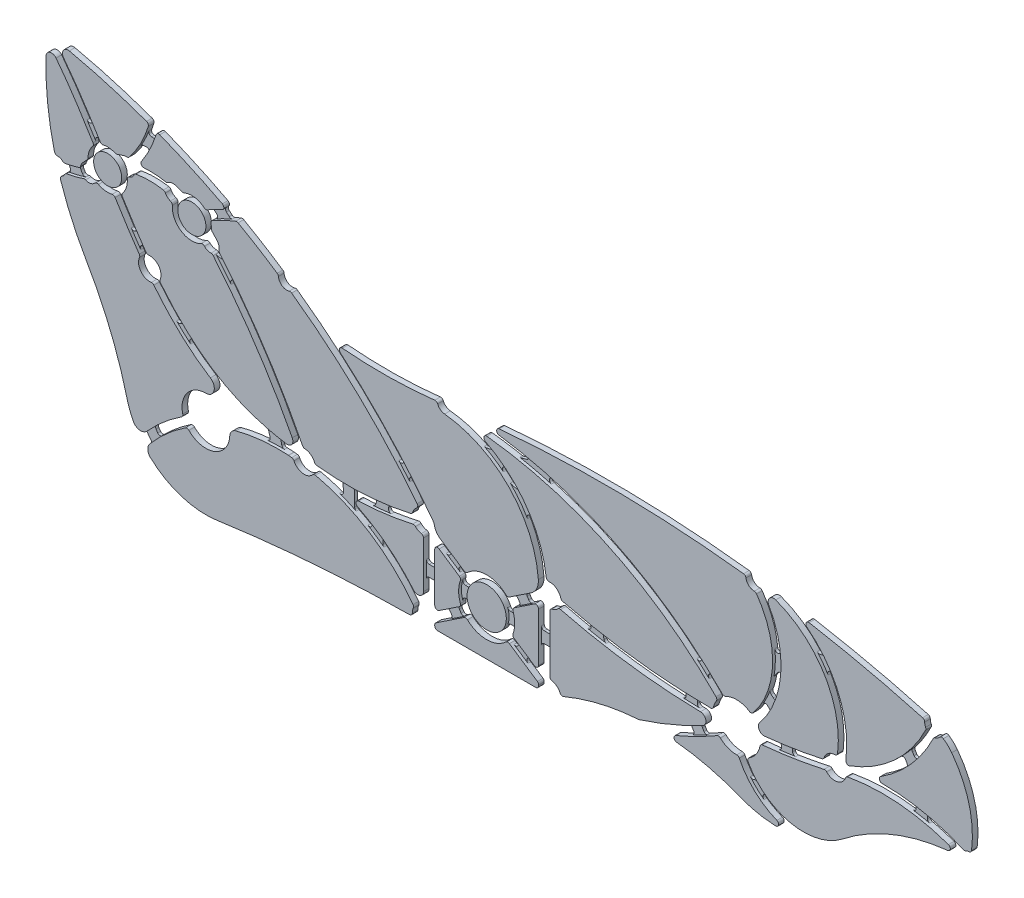
SolidWorks part; units mm, degrees
material "ｴﾎﾟｷｼ樹脂(充填剤なし)"
ref_plane "正面" through (0, 0, 0) normal (0, 0, 1) x (1, 0, 0)
ref_plane "平面" through (0, 0, 0) normal (0, 1, 0) x (1, 0, 0)
ref_plane "右側面" through (0, 0, 0) normal (1, 0, 0) x (0, 0, -1)
sketch "ｽｹｯﾁ1" plane through (0, 0, 0) normal (0, 0, 1) x (1, 0, 0)
  line L1 (22.5, 10.101) -> (22.5, -10.101)
  line L2 (22.5, 10.101) -> (22.5, -10.101)
  line L3 (-22.5, -6.4126) -> (-22.5, 10.101)
  line L4 (-22.5, -6.4126) -> (-22.5, 10.101)
  line L6 (8.081, 7.1901) -> (15.7442, 12.2989)
  line L7 (-16.9453, -9.4941) -> (-9.7451, -4.694)
  line L8 (-18.5, 8.662) -> (-18.5, -8.662)
  line L9 (-9.7451, 4.694) -> (-16.9453, 9.4941)
  line L10 (-16.9453, -9.4941) -> (-9.7451, -4.694)
  line L11 (-18.5, 8.662) -> (-18.5, -8.662)
  line L12 (-9.7451, 4.694) -> (-16.9453, 9.4941)
  line L13 (9.7451, -4.694) -> (16.9453, -9.4941)
  line L14 (16.9453, 9.4941) -> (9.7451, 4.694)
  line L15 (18.5, -8.662) -> (18.5, 8.662)
  line L16 (9.7451, -4.694) -> (16.9453, -9.4941)
  line L17 (16.9453, 9.4941) -> (9.7451, 4.694)
  line L18 (18.5, -8.662) -> (18.5, 8.662)
  line L19 (-16.4885, 12.7951) -> (-8.081, 7.1901)
  line L20 (8.081, 7.1901) -> (15.7442, 12.2989)
  line L21 (-16.4885, 12.7951) -> (-8.081, 7.1901)
  line L25 (-17.5, -16) -> (17.5, -16)
  line L26 (-18.5, -14.6713) -> (-18.5, -15)
  line L27 (-8.081, -7.1901) -> (-18.0547, -13.8392)
  line L28 (18.0547, -13.8392) -> (8.081, -7.1901)
  line L29 (18.5, -15) -> (18.5, -14.6713)
  line L30 (-17.5, -16) -> (17.5, -16)
  line L31 (-18.5, -14.6713) -> (-18.5, -15)
  line L32 (-8.081, -7.1901) -> (-18.0547, -13.8392)
  line L33 (18.0547, -13.8392) -> (8.081, -7.1901)
  line L34 (18.5, -15) -> (18.5, -14.6713)
  circle A11 centre (-105, 67.4812) radius 5
  circle A12 centre (-105, 67.4812) radius 5
  arc A15 (83.2113, 1.2758) -> (89.0603, -0.9998) centre (89, 7.5) ccw
  arc A16 (89.967, -1.5631) -> (89.0603, -0.9998) centre (89.0674, -1.9998) ccw
  arc A17 (89.967, -1.5631) -> (103.3566, -14.0607) centre (112.8701, 9.5532) ccw
  arc A18 (102.9573, -15.9879) -> (103.3566, -14.0607) centre (102.9829, -14.9883) ccw
  arc A19 (90.1176, -13.3365) -> (102.9573, -15.9879) centre (103.9017, 21) ccw
  arc A20 (90.1176, -13.3365) -> (67.6378, -7.8134) centre (59.3978, -89.8605) ccw
  arc A21 (67.3468, -5.898) -> (67.6378, -7.8134) centre (67.7378, -6.8184) ccw
  arc A22 (67.3468, -5.898) -> (82.0317, 1.4104) centre (13.9413, 119.818) ccw
  arc A23 (83.2113, 1.2758) -> (82.0317, 1.4104) centre (82.5302, 0.5435) ccw
  arc A24 (83.2113, 1.2758) -> (89.0603, -0.9998) centre (89, 7.5) ccw
  arc A25 (89.967, -1.5631) -> (89.0603, -0.9998) centre (89.0674, -1.9998) ccw
  arc A26 (89.967, -1.5631) -> (103.3566, -14.0607) centre (112.8701, 9.5532) ccw
  arc A27 (102.9573, -15.9879) -> (103.3566, -14.0607) centre (102.9829, -14.9883) ccw
  arc A28 (90.1176, -13.3365) -> (102.9573, -15.9879) centre (103.9017, 21) ccw
  arc A29 (90.1176, -13.3365) -> (67.6378, -7.8134) centre (59.3978, -89.8605) ccw
  arc A30 (67.3468, -5.898) -> (67.6378, -7.8134) centre (67.7378, -6.8184) ccw
  arc A31 (67.3468, -5.898) -> (82.0317, 1.4104) centre (13.9413, 119.818) ccw
  arc A32 (83.2113, 1.2758) -> (82.0317, 1.4104) centre (82.5302, 0.5435) ccw
  circle A33 centre (-135, 67.4812) radius 5
  arc A34 (129.2694, 15.7) -> (156.3313, 40.2464) centre (111.7928, 62.1584) ccw
  arc A35 (127.926, 16.7675) -> (129.2694, 15.7) centre (128.9173, 16.636) ccw
  arc A36 (127.926, 16.7675) -> (114.0595, 50.8962) centre (91.0356, 21.6602) ccw
  arc A37 (164.4555, 9.0239) -> (128.5785, 11.9436) centre (141.0399, -56.8173) ccw
  arc A38 (164.2263, 7.0873) -> (164.4555, 9.0239) centre (164.1205, 8.0817) ccw
  arc A39 (164.2263, 7.0873) -> (126.7209, -8.1253) centre (172, -65.9175) ccw
  arc A40 (93.0844, -1.0722) -> (126.7209, -8.1253) centre (112.8701, 9.5532) ccw
  arc A41 (93.4427, 0.2535) -> (93.0844, -1.0722) centre (93.9654, -0.5991) ccw
  arc A42 (93.4427, 0.2535) -> (97.334, 5.8282) centre (89, 7.5) ccw
  arc A43 (98.2209, 6.6271) -> (97.334, 5.8282) centre (98.3144, 5.6315) ccw
  arc A44 (98.2209, 6.6271) -> (120.135, 10.059) centre (81.3677, 185.9262) ccw
  arc A45 (121.0802, 9.766) -> (120.135, 10.059) centre (120.3503, 9.0824) ccw
  arc A46 (121.0802, 9.766) -> (127.8055, 11.2677) centre (124, 12.5) ccw
  arc A47 (128.5785, 11.9436) -> (127.8055, 11.2677) centre (128.7568, 10.9597) ccw
  arc A48 (164.4555, 9.0239) -> (128.5785, 11.9436) centre (141.0399, -56.8173) ccw
  arc A49 (164.2263, 7.0873) -> (164.4555, 9.0239) centre (164.1205, 8.0817) ccw
  arc A50 (164.2263, 7.0873) -> (126.7209, -8.1253) centre (172, -65.9175) ccw
  arc A51 (93.0844, -1.0722) -> (126.7209, -8.1253) centre (112.8701, 9.5532) ccw
  arc A52 (93.4427, 0.2535) -> (93.0844, -1.0722) centre (93.9654, -0.5991) ccw
  arc A53 (93.4427, 0.2535) -> (97.334, 5.8282) centre (89, 7.5) ccw
  arc A54 (98.2209, 6.6271) -> (97.334, 5.8282) centre (98.3144, 5.6315) ccw
  arc A55 (98.2209, 6.6271) -> (120.135, 10.059) centre (81.3677, 185.9262) ccw
  arc A56 (121.0802, 9.766) -> (120.135, 10.059) centre (120.3503, 9.0824) ccw
  arc A57 (121.0802, 9.766) -> (127.8055, 11.2677) centre (124, 12.5) ccw
  arc A58 (128.5785, 11.9436) -> (127.8055, 11.2677) centre (128.7568, 10.9597) ccw
  arc A59 (114.85, 52.6669) -> (114.0595, 50.8962) centre (114.6782, 51.6818) ccw
  arc A60 (155.2686, 43.5545) -> (114.85, 52.6669) centre (42.29, -363.3692) ccw
  arc A61 (156.0008, 42.5682) -> (155.2686, 43.5545) centre (155.001, 42.5909) ccw
  arc A62 (156.0008, 42.5682) -> (156.3255, 41.1409) centre (159, 42.5) ccw
  arc A63 (156.3313, 40.2464) -> (156.3255, 41.1409) centre (155.434, 40.6879) ccw
  arc A64 (129.2694, 15.7) -> (156.3313, 40.2464) centre (111.7928, 62.1584) ccw
  arc A65 (127.926, 16.7675) -> (129.2694, 15.7) centre (128.9173, 16.636) ccw
  arc A66 (127.926, 16.7675) -> (114.0595, 50.8962) centre (91.0356, 21.6602) ccw
  arc A67 (114.85, 52.6669) -> (114.0595, 50.8962) centre (114.6782, 51.6818) ccw
  arc A68 (155.2686, 43.5545) -> (114.85, 52.6669) centre (42.29, -363.3692) ccw
  arc A69 (156.0008, 42.5682) -> (155.2686, 43.5545) centre (155.001, 42.5909) ccw
  arc A70 (156.0008, 42.5682) -> (156.3255, 41.1409) centre (159, 42.5) ccw
  arc A71 (156.3313, 40.2464) -> (156.3255, 41.1409) centre (155.434, 40.6879) ccw
  arc A72 (97.2256, 12.9693) -> (98.9735, 9.7142) centre (98.7746, 11.7043) ccw
  arc A73 (97.2256, 12.9693) -> (100.5051, 50.879) centre (71.0713, 34.3286) ccw
  arc A74 (93.5868, 14.6562) -> (85.0963, 15.0506) centre (89, 7.5) ccw
  arc A75 (171.786, 10.4924) -> (170.6448, 10.1764) centre (172, 7.5) ccw
  arc A76 (169.7984, 10.1497) -> (170.6448, 10.1764) centre (170.193, 11.0686) ccw
  arc A77 (169.7984, 10.1497) -> (140.836, 16.0634) centre (141.0399, -56.8173) ccw
  arc A78 (140.2918, 17.9041) -> (140.836, 16.0634) centre (140.8332, 17.0634) ccw
  arc A79 (140.2918, 17.9041) -> (159.0925, 39.0635) centre (111.7928, 62.1584) ccw
  arc A80 (159.7433, 39.5935) -> (159.0925, 39.0635) centre (159.9911, 38.6247) ccw
  arc A81 (159.7433, 39.5935) -> (161.317, 40.5944) centre (159, 42.5) ccw
  arc A82 (162.6526, 40.7855) -> (161.317, 40.5944) centre (162.0894, 39.9592) ccw
  arc A83 (165.6353, 37.9447) -> (162.6526, 40.7855) centre (155.4945, 30.2837) ccw
  arc A84 (172.7066, 11.3632) -> (165.6353, 37.9447) centre (136.5587, 15.9784) ccw
  arc A85 (171.786, 10.4924) -> (172.7066, 11.3632) centre (171.7146, 11.4898) ccw
  arc A86 (171.786, 10.4924) -> (170.6448, 10.1764) centre (172, 7.5) ccw
  arc A87 (169.7984, 10.1497) -> (170.6448, 10.1764) centre (170.193, 11.0686) ccw
  arc A88 (169.7984, 10.1497) -> (140.836, 16.0634) centre (141.0399, -56.8173) ccw
  arc A89 (140.2918, 17.9041) -> (140.836, 16.0634) centre (140.8332, 17.0634) ccw
  arc A90 (140.2918, 17.9041) -> (159.0925, 39.0635) centre (111.7928, 62.1584) ccw
  arc A91 (159.7433, 39.5935) -> (159.0925, 39.0635) centre (159.9911, 38.6247) ccw
  arc A92 (159.7433, 39.5935) -> (161.317, 40.5944) centre (159, 42.5) ccw
  arc A93 (162.6526, 40.7855) -> (161.317, 40.5944) centre (162.0894, 39.9592) ccw
  arc A94 (165.6353, 37.9447) -> (162.6526, 40.7855) centre (155.4945, 30.2837) ccw
  arc A95 (172.7066, 11.3632) -> (165.6353, 37.9447) centre (136.5587, 15.9784) ccw
  arc A96 (171.786, 10.4924) -> (172.7066, 11.3632) centre (171.7146, 11.4898) ccw
  arc A97 (83.9236, 15.238) -> (85.0963, 15.0506) centre (84.637, 15.9389) ccw
  arc A98 (83.9236, 15.238) -> (4.4224, 55.2639) centre (-14.6672, -81.6202) ccw
  arc A99 (4.471, 57.2503) -> (4.4224, 55.2639) centre (4.5606, 56.2543) ccw
  arc A100 (91.4838, 56.0721) -> (4.471, 57.2503) centre (42.29, -363.3692) ccw
  arc A101 (92.3587, 55.2099) -> (91.4838, 56.0721) centre (91.3673, 55.0789) ccw
  arc A102 (92.3587, 55.2099) -> (95.319, 52.6028) centre (95.3328, 55.6027) ccw
  arc A103 (96.1287, 52.1831) -> (95.319, 52.6028) centre (95.3143, 51.6028) ccw
  arc A104 (94.9009, 14.8656) -> (96.1287, 52.1831) centre (71.0713, 34.3286) ccw
  arc A105 (93.5868, 14.6562) -> (94.9009, 14.8656) centre (94.1264, 15.4981) ccw
  arc A106 (93.5868, 14.6562) -> (85.0963, 15.0506) centre (89, 7.5) ccw
  arc A107 (83.9236, 15.238) -> (85.0963, 15.0506) centre (84.637, 15.9389) ccw
  arc A108 (83.9236, 15.238) -> (4.4224, 55.2639) centre (-14.6672, -81.6202) ccw
  arc A109 (4.471, 57.2503) -> (4.4224, 55.2639) centre (4.5606, 56.2543) ccw
  arc A110 (91.4838, 56.0721) -> (4.471, 57.2503) centre (42.29, -363.3692) ccw
  arc A111 (92.3587, 55.2099) -> (91.4838, 56.0721) centre (91.3673, 55.0789) ccw
  arc A112 (92.3587, 55.2099) -> (95.319, 52.6028) centre (95.3328, 55.6027) ccw
  arc A113 (96.1287, 52.1831) -> (95.319, 52.6028) centre (95.3143, 51.6028) ccw
  arc A114 (94.9009, 14.8656) -> (96.1287, 52.1831) centre (71.0713, 34.3286) ccw
  arc A115 (93.5868, 14.6562) -> (94.9009, 14.8656) centre (94.1264, 15.4981) ccw
  arc A116 (81.6673, 13.2539) -> (0.0815, 52.7818) centre (-14.6672, -81.6202) ccw
  arc A117 (81.8017, 12.0204) -> (81.6673, 13.2539) centre (80.9548, 12.5522) ccw
  arc A118 (81.8017, 12.0204) -> (80.7533, 9.5597) centre (89, 7.5) ccw
  arc A119 (79.7833, 8.8021) -> (80.7533, 9.5597) centre (79.7831, 9.8021) ccw
  arc A120 (27.0791, 15.346) -> (79.7833, 8.8021) centre (79.7405, 223.9658) ccw
  arc A121 (26.3591, 16.0525) -> (27.0791, 15.346) centre (27.3238, 16.3156) ccw
  arc A122 (26.3591, 16.0525) -> (22.2579, 18.9927) centre (22.5, 15) ccw
  arc A123 (21.2047, 19.87) -> (22.2579, 18.9927) centre (22.1973, 19.9908) ccw
  arc A124 (21.2047, 19.87) -> (-0.4821, 50.897) centre (-18.8012, 15) ccw
  arc A125 (0.0815, 52.7818) -> (-0.4821, 50.897) centre (-0.0275, 51.7877) ccw
  arc A126 (81.6673, 13.2539) -> (0.0815, 52.7818) centre (-14.6672, -81.6202) ccw
  arc A127 (81.8017, 12.0204) -> (81.6673, 13.2539) centre (80.9548, 12.5522) ccw
  arc A128 (81.8017, 12.0204) -> (80.7533, 9.5597) centre (89, 7.5) ccw
  arc A129 (79.7833, 8.8021) -> (80.7533, 9.5597) centre (79.7831, 9.8021) ccw
  arc A130 (27.0791, 15.346) -> (79.7833, 8.8021) centre (79.7405, 223.9658) ccw
  arc A131 (26.3591, 16.0525) -> (27.0791, 15.346) centre (27.3238, 16.3156) ccw
  arc A132 (26.3591, 16.0525) -> (22.2579, 18.9927) centre (22.5, 15) ccw
  arc A133 (21.2047, 19.87) -> (22.2579, 18.9927) centre (22.1973, 19.9908) ccw
  arc A134 (21.2047, 19.87) -> (-0.4821, 50.897) centre (-18.8012, 15) ccw
  arc A135 (0.0815, 52.7818) -> (-0.4821, 50.897) centre (-0.0275, 51.7877) ccw
  arc A136 (102.9446, 53.7342) -> (100.5051, 50.879) centre (102.2484, 51.8592) ccw
  arc A137 (23.3, 11.0808) -> (25.3408, 12.184) centre (22.5, 15) ccw
  arc A138 (26.296, 12.4496) -> (25.3408, 12.184) centre (26.0511, 11.4801) ccw
  arc A139 (26.296, 12.4496) -> (76.128, 5.832) centre (79.7405, 223.9658) ccw
  arc A140 (77.0395, 2.0694) -> (76.128, 5.832) centre (76.0949, 3.8322) ccw
  arc A141 (54.3014, -7.5287) -> (77.0395, 2.0694) centre (13.9413, 119.818) ccw
  arc A142 (54.0639, -7.5734) -> (54.3014, -7.5287) centre (53.9993, -6.5755) ccw
  arc A143 (54.0639, -7.5734) -> (27.4366, -13.8466) centre (59.3978, -89.8605) ccw
  arc A144 (26.1392, -13.3399) -> (27.4366, -13.8466) centre (27.049, -12.9248) ccw
  arc A145 (26.1392, -13.3399) -> (23.3, -11.0808) centre (22.5, -15) ccw
  arc A146 (22.5, -10.101) -> (23.3, -11.0808) centre (23.5, -10.101) ccw
  arc A147 (23.3, 11.0808) -> (22.5, 10.101) centre (23.5, 10.101) ccw
  arc A148 (23.3, 11.0808) -> (25.3408, 12.184) centre (22.5, 15) ccw
  arc A149 (26.296, 12.4496) -> (25.3408, 12.184) centre (26.0511, 11.4801) ccw
  arc A150 (26.296, 12.4496) -> (76.128, 5.832) centre (79.7405, 223.9658) ccw
  arc A151 (77.0395, 2.0694) -> (76.128, 5.832) centre (76.0949, 3.8322) ccw
  arc A152 (54.3014, -7.5287) -> (77.0395, 2.0694) centre (13.9413, 119.818) ccw
  arc A153 (54.0639, -7.5734) -> (54.3014, -7.5287) centre (53.9993, -6.5755) ccw
  arc A154 (54.0639, -7.5734) -> (27.4366, -13.8466) centre (59.3978, -89.8605) ccw
  arc A155 (26.1392, -13.3399) -> (27.4366, -13.8466) centre (27.049, -12.9248) ccw
  arc A156 (26.1392, -13.3399) -> (23.3, -11.0808) centre (22.5, -15) ccw
  arc A157 (22.5, -10.101) -> (23.3, -11.0808) centre (23.5, -10.101) ccw
  arc A158 (23.3, 11.0808) -> (22.5, 10.101) centre (23.5, 10.101) ccw
  arc A159 (124.9796, 17.3747) -> (102.9446, 53.7342) centre (91.0356, 21.6602) ccw
  arc A160 (123.99, 16.5) -> (124.9796, 17.3747) centre (123.9875, 17.5) ccw
  arc A161 (123.99, 16.5) -> (120.1725, 13.6619) centre (124, 12.5) ccw
  arc A162 (119.4305, 12.9757) -> (120.1725, 13.6619) centre (119.2156, 13.9524) ccw
  arc A163 (98.9735, 9.7142) -> (119.4305, 12.9757) centre (81.3677, 185.9262) ccw
  arc A164 (97.2256, 12.9693) -> (98.9735, 9.7142) centre (98.7746, 11.7043) ccw
  arc A165 (97.2256, 12.9693) -> (100.5051, 50.879) centre (71.0713, 34.3286) ccw
  arc A166 (102.9446, 53.7342) -> (100.5051, 50.879) centre (102.2484, 51.8592) ccw
  arc A167 (124.9796, 17.3747) -> (102.9446, 53.7342) centre (91.0356, 21.6602) ccw
  arc A168 (123.99, 16.5) -> (124.9796, 17.3747) centre (123.9875, 17.5) ccw
  arc A169 (123.99, 16.5) -> (120.1725, 13.6619) centre (124, 12.5) ccw
  arc A170 (119.4305, 12.9757) -> (120.1725, 13.6619) centre (119.2156, 13.9524) ccw
  arc A171 (98.9735, 9.7142) -> (119.4305, 12.9757) centre (81.3677, 185.9262) ccw
  circle A172 centre (-135, 67.4812) radius 5
  arc A179 (-9.3634, 3.5108) -> (-9.3634, -3.5108) centre (0, 0) ccw
  arc A180 (-9.7451, -4.694) -> (-9.3634, -3.5108) centre (-10.2998, -3.8619) ccw
  arc A181 (-25.3716, 12.2154) -> (-23.3, 11.0808) centre (-22.5, 15) ccw
  arc A182 (-22.5, 10.101) -> (-23.3, 11.0808) centre (-23.5, 10.101) ccw
  arc A183 (-26.0294, -7.7013) -> (-22.5, -6.4126) centre (-24.5, -6.4126) ccw
  arc A184 (-150.1749, 61.8391) -> (-145.3174, 63.0063) centre (-156.5, 98.8544) ccw
  arc A185 (-150.9937, 62.0651) -> (-150.1749, 61.8391) centre (-150.3434, 62.8248) ccw
  arc A186 (-150.9937, 62.0651) -> (-152.9688, 62.786) centre (-152.9445, 59.7861) ccw
  arc A187 (-153.9477, 63.5462) -> (-152.9688, 62.786) centre (-152.9768, 63.786) ccw
  arc A188 (-156.9598, 91.5374) -> (-153.9477, 63.5462) centre (-52.35, 88.6367) ccw
  arc A189 (-153.381, 92.7088) -> (-156.9598, 91.5374) centre (-154.9606, 91.482) ccw
  arc A190 (-140.3222, 72.0281) -> (-140.2301, 73.2004) centre (-141.0826, 72.6776) ccw
  arc A191 (-140.3222, 72.0281) -> (-141.9993, 67.5789) centre (-135, 67.4812) ccw
  arc A192 (-142.2946, 66.8832) -> (-141.9993, 67.5789) centre (-142.9992, 67.5928) ccw
  arc A193 (-89.4045, 74.3517) -> (-97.7506, 70.3671) centre (-65, 12.5) ccw
  arc A194 (-88.5457, 74.2922) -> (-89.4045, 74.3517) centre (-89.0375, 73.4215) ccw
  arc A195 (-74.6081, 65.7118) -> (-88.5457, 74.2922) centre (-195.2577, -114.6564) ccw
  arc A196 (-74.1672, 64.9589) -> (-74.6081, 65.7118) centre (-75.1641, 64.8806) ccw
  arc A197 (-74.1672, 64.9589) -> (-70.3341, 62.3144) centre (-71.1764, 65.1938) ccw
  arc A198 (-69.4737, 62.1695) -> (-70.3341, 62.3144) centre (-70.0534, 61.3546) ccw
  arc A199 (-24.7617, 19.5826) -> (-69.4737, 62.1695) centre (-195.2577, -114.6564) ccw
  arc A200 (-24.9379, 18.1712) -> (-24.7617, 19.5826) centre (-25.5474, 18.964) ccw
  arc A201 (-24.9379, 18.1712) -> (-26.3471, 16.0955) centre (-22.5, 15) ccw
  arc A202 (-27.086, 15.3946) -> (-26.3471, 16.0955) centre (-27.3088, 16.3694) ccw
  arc A203 (-60.4919, 13.4295) -> (-27.086, 15.3946) centre (-49.6549, 114.1334) ccw
  arc A204 (-61.3079, 14.039) -> (-60.4919, 13.4295) centre (-60.3849, 14.4238) ccw
  arc A205 (-61.3079, 14.039) -> (-64.7539, 16.4924) centre (-65, 12.5) ccw
  arc A206 (-65.5834, 17.0366) -> (-64.7539, 16.4924) centre (-64.6924, 17.4905) ccw
  arc A207 (-65.5834, 17.0366) -> (-95.1344, 61.7139) centre (-276.8279, -90.5756) ccw
  arc A208 (-95.3497, 62.5466) -> (-95.1344, 61.7139) centre (-94.368, 62.3562) ccw
  arc A209 (-95.3497, 62.5466) -> (-96.0213, 65.0748) centre (-98.2949, 63.1176) ccw
  arc A210 (-96.0213, 65.0748) -> (-97.7054, 66.8832) centre (-120, 44.4324) ccw
  arc A211 (-98.0007, 67.5789) -> (-97.7054, 66.8832) centre (-97.0008, 67.5928) ccw
  arc A212 (-98.0007, 67.5789) -> (-98.2258, 69.2449) centre (-105, 67.4812) ccw
  arc A213 (-97.7506, 70.3671) -> (-98.2258, 69.2449) centre (-97.2581, 69.4969) ccw
  arc A214 (-89.4045, 74.3517) -> (-97.7506, 70.3671) centre (-65, 12.5) ccw
  arc A215 (-88.5457, 74.2922) -> (-89.4045, 74.3517) centre (-89.0375, 73.4215) ccw
  arc A216 (-74.6081, 65.7118) -> (-88.5457, 74.2922) centre (-195.2577, -114.6564) ccw
  arc A217 (-74.1672, 64.9589) -> (-74.6081, 65.7118) centre (-75.1641, 64.8806) ccw
  arc A218 (-74.1672, 64.9589) -> (-70.3341, 62.3144) centre (-71.1764, 65.1938) ccw
  arc A219 (-69.4737, 62.1695) -> (-70.3341, 62.3144) centre (-70.0534, 61.3546) ccw
  arc A220 (-24.7617, 19.5826) -> (-69.4737, 62.1695) centre (-195.2577, -114.6564) ccw
  arc A221 (-24.9379, 18.1712) -> (-24.7617, 19.5826) centre (-25.5474, 18.964) ccw
  arc A222 (-24.9379, 18.1712) -> (-26.3471, 16.0955) centre (-22.5, 15) ccw
  arc A223 (-27.086, 15.3946) -> (-26.3471, 16.0955) centre (-27.3088, 16.3694) ccw
  arc A224 (-60.4919, 13.4295) -> (-27.086, 15.3946) centre (-49.6549, 114.1334) ccw
  arc A225 (-61.3079, 14.039) -> (-60.4919, 13.4295) centre (-60.3849, 14.4238) ccw
  arc A226 (-61.3079, 14.039) -> (-64.7539, 16.4924) centre (-65, 12.5) ccw
  arc A227 (-65.5834, 17.0366) -> (-64.7539, 16.4924) centre (-64.6924, 17.4905) ccw
  arc A228 (-65.5834, 17.0366) -> (-95.1344, 61.7139) centre (-276.8279, -90.5756) ccw
  arc A229 (-95.3497, 62.5466) -> (-95.1344, 61.7139) centre (-94.368, 62.3562) ccw
  arc A230 (-95.3497, 62.5466) -> (-96.0213, 65.0748) centre (-98.2949, 63.1176) ccw
  arc A231 (-96.0213, 65.0748) -> (-97.7054, 66.8832) centre (-120, 44.4324) ccw
  arc A232 (-98.0007, 67.5789) -> (-97.7054, 66.8832) centre (-97.0008, 67.5928) ccw
  arc A233 (-98.0007, 67.5789) -> (-98.2258, 69.2449) centre (-105, 67.4812) ccw
  arc A234 (-97.7506, 70.3671) -> (-98.2258, 69.2449) centre (-97.2581, 69.4969) ccw
  arc A235 (-142.2946, 66.8832) -> (-143.9787, 65.0748) centre (-120, 44.4324) ccw
  arc A236 (-143.9787, 65.0748) -> (-144.6377, 63.7501) centre (-141.7051, 63.1176) ccw
  arc A237 (-145.3174, 63.0063) -> (-144.6377, 63.7501) centre (-145.6152, 63.9609) ccw
  arc A238 (-150.1749, 61.8391) -> (-145.3174, 63.0063) centre (-156.5, 98.8544) ccw
  arc A239 (-150.9937, 62.0651) -> (-150.1749, 61.8391) centre (-150.3434, 62.8248) ccw
  arc A240 (-150.9937, 62.0651) -> (-152.9688, 62.786) centre (-152.9445, 59.7861) ccw
  arc A241 (-153.9477, 63.5462) -> (-152.9688, 62.786) centre (-152.9768, 63.786) ccw
  arc A242 (-156.9598, 91.5374) -> (-153.9477, 63.5462) centre (-52.35, 88.6367) ccw
  arc A243 (-153.381, 92.7088) -> (-156.9598, 91.5374) centre (-154.9606, 91.482) ccw
  arc A244 (-140.3222, 72.0281) -> (-140.2301, 73.2004) centre (-141.0826, 72.6776) ccw
  arc A245 (-140.3222, 72.0281) -> (-141.9993, 67.5789) centre (-135, 67.4812) ccw
  arc A246 (-142.2946, 66.8832) -> (-141.9993, 67.5789) centre (-142.9992, 67.5928) ccw
  arc A247 (-142.2946, 66.8832) -> (-143.9787, 65.0748) centre (-120, 44.4324) ccw
  arc A248 (-143.9787, 65.0748) -> (-144.6377, 63.7501) centre (-141.7051, 63.1176) ccw
  arc A249 (-145.3174, 63.0063) -> (-144.6377, 63.7501) centre (-145.6152, 63.9609) ccw
  arc A250 (-26.0294, -7.7013) -> (-46.0024, 8.0337) centre (-74.1755, -48.2713) ccw
  arc A251 (-45.5939, 9.9272) -> (-46.0024, 8.0337) centre (-45.555, 8.9279) ccw
  arc A252 (-45.5939, 9.9272) -> (-26.3133, 12.4939) centre (-49.6549, 114.1334) ccw
  arc A253 (-122.9601, 76.0613) -> (-117.7547, 86.8856) centre (-156.5, 98.8544) ccw
  arc A254 (-116.4361, 87.5221) -> (-117.7547, 86.8856) centre (-116.7993, 86.5904) ccw
  arc A255 (-94.1545, 77.3518) -> (-116.4361, 87.5221) centre (-195.2577, -114.6564) ccw
  arc A256 (-94.2003, 75.5596) -> (-94.1545, 77.3518) centre (-94.6204, 76.467) ccw
  arc A257 (-94.2003, 75.5596) -> (-99.4771, 72.8365) centre (-65, 12.5) ccw
  arc A258 (-100.6016, 72.9268) -> (-99.4771, 72.8365) centre (-99.9733, 73.7047) ccw
  arc A259 (-100.6016, 72.9268) -> (-107.7452, 73.9205) centre (-105, 67.4812) ccw
  arc A260 (-108.5008, 73.9088) -> (-107.7452, 73.9205) centre (-108.1373, 74.8404) ccw
  arc A261 (-108.5008, 73.9088) -> (-110.8362, 74.7163) centre (-120, 44.4324) ccw
  arc A262 (-110.8362, 74.7163) -> (-113.5331, 74.2236) centre (-111.7051, 71.8449) ccw
  arc A263 (-114.3306, 74.0344) -> (-113.5331, 74.2236) centre (-114.1425, 75.0165) ccw
  arc A264 (-114.3306, 74.0344) -> (-122.0645, 74.5016) centre (-120, 44.4324) ccw
  arc A265 (-122.9601, 76.0613) -> (-122.0645, 74.5016) centre (-122.133, 75.4992) ccw
  arc A266 (-122.9601, 76.0613) -> (-117.7547, 86.8856) centre (-156.5, 98.8544) ccw
  arc A267 (-116.4361, 87.5221) -> (-117.7547, 86.8856) centre (-116.7993, 86.5904) ccw
  arc A268 (-94.1545, 77.3518) -> (-116.4361, 87.5221) centre (-195.2577, -114.6564) ccw
  arc A269 (-94.2003, 75.5596) -> (-94.1545, 77.3518) centre (-94.6204, 76.467) ccw
  arc A270 (-94.2003, 75.5596) -> (-99.4771, 72.8365) centre (-65, 12.5) ccw
  arc A271 (-100.6016, 72.9268) -> (-99.4771, 72.8365) centre (-99.9733, 73.7047) ccw
  arc A272 (-100.6016, 72.9268) -> (-107.7452, 73.9205) centre (-105, 67.4812) ccw
  arc A273 (-108.5008, 73.9088) -> (-107.7452, 73.9205) centre (-108.1373, 74.8404) ccw
  arc A274 (-108.5008, 73.9088) -> (-110.8362, 74.7163) centre (-120, 44.4324) ccw
  arc A275 (-110.8362, 74.7163) -> (-113.5331, 74.2236) centre (-111.7051, 71.8449) ccw
  arc A276 (-114.3306, 74.0344) -> (-113.5331, 74.2236) centre (-114.1425, 75.0165) ccw
  arc A277 (-114.3306, 74.0344) -> (-122.0645, 74.5016) centre (-120, 44.4324) ccw
  arc A278 (-122.9601, 76.0613) -> (-122.0645, 74.5016) centre (-122.133, 75.4992) ccw
  arc A279 (-25.3716, 12.2154) -> (-26.3133, 12.4939) centre (-26.0895, 11.5192) ccw
  arc A280 (-25.3716, 12.2154) -> (-23.3, 11.0808) centre (-22.5, 15) ccw
  arc A281 (-22.5, 10.101) -> (-23.3, 11.0808) centre (-23.5, 10.101) ccw
  arc A282 (-26.0294, -7.7013) -> (-22.5, -6.4126) centre (-24.5, -6.4126) ccw
  arc A283 (-106.0705, 1.5503) -> (-91.5134, 7.0221) centre (-100, 7.5) ccw
  arc A284 (-89.2736, 9.7568) -> (-91.5134, 7.0221) centre (-88.5182, 6.8535) ccw
  arc A285 (-70.6217, 11.5834) -> (-89.2736, 9.7568) centre (-74.1755, -48.2713) ccw
  arc A286 (-70.544, 11.5757) -> (-70.6217, 11.5834) centre (-70.681, 10.5851) ccw
  arc A287 (-70.544, 11.5757) -> (-69.4318, 11.4299) centre (-59.6286, 90.5152) ccw
  arc A288 (-68.6438, 10.85) -> (-69.4318, 11.4299) centre (-69.5548, 10.4375) ccw
  arc A289 (-68.6438, 10.85) -> (-61.9641, 9.8955) centre (-65, 12.5) ccw
  arc A290 (-60.9851, 10.2199) -> (-61.9641, 9.8955) centre (-61.2051, 9.2444) ccw
  arc A291 (-26.225, -12.2719) -> (-60.9851, 10.2199) centre (-74.1755, -48.2713) ccw
  arc A292 (-26.1198, -13.2978) -> (-26.225, -12.2719) centre (-27.0247, -12.8723) ccw
  arc A293 (-26.1198, -13.2978) -> (-26.5, -15.0192) centre (-22.5, -15) ccw
  arc A294 (-27.4903, -16.024) -> (-26.5, -15.0192) centre (-27.4999, -15.024) ccw
  arc A295 (-27.4903, -16.024) -> (-95.9045, -21.2094) centre (-22.5, -535.7727) ccw
  arc A296 (-119.7512, -13.7341) -> (-95.9045, -21.2094) centre (-100, 7.5) ccw
  arc A297 (-120.0008, -9.6028) -> (-119.7512, -13.7341) centre (-117.708, -11.5375) ccw
  arc A298 (-107.3377, 1.6835) -> (-120.0008, -9.6028) centre (-74.1755, -48.2713) ccw
  arc A299 (-106.0705, 1.5503) -> (-107.3377, 1.6835) centre (-106.7847, 0.8503) ccw
  arc A300 (-106.0705, 1.5503) -> (-91.5134, 7.0221) centre (-100, 7.5) ccw
  arc A301 (-89.2736, 9.7568) -> (-91.5134, 7.0221) centre (-88.5182, 6.8535) ccw
  arc A302 (-70.6217, 11.5834) -> (-89.2736, 9.7568) centre (-74.1755, -48.2713) ccw
  arc A303 (-70.544, 11.5757) -> (-70.6217, 11.5834) centre (-70.681, 10.5851) ccw
  arc A304 (-70.544, 11.5757) -> (-69.4318, 11.4299) centre (-59.6286, 90.5152) ccw
  arc A305 (-68.6438, 10.85) -> (-69.4318, 11.4299) centre (-69.5548, 10.4375) ccw
  arc A306 (-68.6438, 10.85) -> (-61.9641, 9.8955) centre (-65, 12.5) ccw
  arc A307 (-60.9851, 10.2199) -> (-61.9641, 9.8955) centre (-61.2051, 9.2444) ccw
  arc A308 (-26.225, -12.2719) -> (-60.9851, 10.2199) centre (-74.1755, -48.2713) ccw
  arc A309 (-26.1198, -13.2978) -> (-26.225, -12.2719) centre (-27.0247, -12.8723) ccw
  arc A310 (-26.1198, -13.2978) -> (-26.5, -15.0192) centre (-22.5, -15) ccw
  arc A311 (-27.4903, -16.024) -> (-26.5, -15.0192) centre (-27.4999, -15.024) ccw
  arc A312 (-27.4903, -16.024) -> (-95.9045, -21.2094) centre (-22.5, -535.7727) ccw
  arc A313 (-119.7512, -13.7341) -> (-95.9045, -21.2094) centre (-100, 7.5) ccw
  arc A314 (-120.0008, -9.6028) -> (-119.7512, -13.7341) centre (-117.708, -11.5375) ccw
  arc A315 (-107.3377, 1.6835) -> (-120.0008, -9.6028) centre (-74.1755, -48.2713) ccw
  arc A316 (-106.0705, 1.5503) -> (-107.3377, 1.6835) centre (-106.7847, 0.8503) ccw
  arc A317 (-26.0294, -7.7013) -> (-46.0024, 8.0337) centre (-74.1755, -48.2713) ccw
  arc A318 (-45.5939, 9.9272) -> (-46.0024, 8.0337) centre (-45.555, 8.9279) ccw
  arc A319 (-45.5939, 9.9272) -> (-26.3133, 12.4939) centre (-49.6549, 114.1334) ccw
  arc A320 (-25.3716, 12.2154) -> (-26.3133, 12.4939) centre (-26.0895, 11.5192) ccw
  arc A321 (-18.5, -8.662) -> (-16.9453, -9.4941) centre (-17.5, -8.662) ccw
  arc A322 (-16.9453, 9.4941) -> (-18.5, 8.662) centre (-17.5, 8.662) ccw
  arc A323 (-9.3634, 3.5108) -> (-9.7451, 4.694) centre (-10.2998, 3.8619) ccw
  arc A324 (-148.6552, 97.2804) -> (-150.6693, 94.1069) centre (-149.0847, 95.3271) ccw
  arc A325 (-121.1468, 89.296) -> (-148.6552, 97.2804) centre (-195.2577, -114.6564) ccw
  arc A326 (-120.5304, 88.0689) -> (-121.1468, 89.296) centre (-121.4883, 88.3561) ccw
  arc A327 (-127.3262, 75.2106) -> (-120.5304, 88.0689) centre (-156.5, 98.8544) ccw
  arc A328 (-128.151, 74.8414) -> (-127.3262, 75.2106) centre (-128.1031, 75.8403) ccw
  arc A329 (-128.151, 74.8414) -> (-129.1638, 74.7163) centre (-128.2949, 71.8449) ccw
  arc A330 (-129.1638, 74.7163) -> (-131.4992, 73.9088) centre (-120, 44.4324) ccw
  arc A331 (-132.2548, 73.9205) -> (-131.4992, 73.9088) centre (-131.8627, 74.8404) ccw
  arc A332 (-100.5079, 61.0921) -> (-98.2079, 60.1189) centre (-98.2949, 63.1176) ccw
  arc A333 (-97.4124, 59.7615) -> (-98.2079, 60.1189) centre (-98.1789, 59.1193) ccw
  arc A334 (-69.2613, 17.6245) -> (-97.4124, 59.7615) centre (-276.8279, -90.5756) ccw
  arc A335 (-71.3387, 14.7232) -> (-69.2613, 17.6245) centre (-71.0348, 16.7) ccw
  arc A336 (-116.298, 42.9173) -> (-116.1523, 41.9125) centre (-115.3725, 42.5386) ccw
  arc A337 (-116.298, 42.9173) -> (-120.4138, 48.4109) centre (-120, 44.4324) ccw
  arc A338 (-121.3351, 48.83) -> (-120.4138, 48.4109) centre (-120.5173, 49.4055) ccw
  arc A339 (-129.673, 62.9399) -> (-129.7634, 61.7667) centre (-128.912, 62.2912) ccw
  arc A340 (-129.673, 62.9399) -> (-128.0179, 67.9818) centre (-135, 67.4812) ccw
  arc A341 (-127.3391, 69.0012) -> (-128.0179, 67.9818) centre (-127.0205, 68.0533) ccw
  arc A342 (-127.3391, 69.0012) -> (-125.5769, 70.575) centre (-128.2949, 71.8449) ccw
  arc A343 (-124.8496, 71.1356) -> (-125.5769, 70.575) centre (-124.6709, 70.1517) ccw
  arc A344 (-115.1504, 71.1356) -> (-124.8496, 71.1356) centre (-120, 44.4324) ccw
  arc A345 (-114.4231, 70.575) -> (-115.1504, 71.1356) centre (-115.3291, 70.1517) ccw
  arc A346 (-114.4231, 70.575) -> (-112.6609, 69.0012) centre (-111.7051, 71.8449) ccw
  arc A347 (-111.9821, 67.9818) -> (-112.6609, 69.0012) centre (-112.9795, 68.0533) ccw
  arc A348 (-111.9821, 67.9818) -> (-101.7149, 61.3) centre (-105, 67.4812) ccw
  arc A349 (-100.5079, 61.0921) -> (-101.7149, 61.3) centre (-101.2456, 60.4169) ccw
  arc A350 (-100.5079, 61.0921) -> (-98.2079, 60.1189) centre (-98.2949, 63.1176) ccw
  arc A351 (-97.4124, 59.7615) -> (-98.2079, 60.1189) centre (-98.1789, 59.1193) ccw
  arc A352 (-69.2613, 17.6245) -> (-97.4124, 59.7615) centre (-276.8279, -90.5756) ccw
  arc A353 (-71.3387, 14.7232) -> (-69.2613, 17.6245) centre (-71.0348, 16.7) ccw
  arc A354 (-116.298, 42.9173) -> (-116.1523, 41.9125) centre (-115.3725, 42.5386) ccw
  arc A355 (-116.298, 42.9173) -> (-120.4138, 48.4109) centre (-120, 44.4324) ccw
  arc A356 (-121.3351, 48.83) -> (-120.4138, 48.4109) centre (-120.5173, 49.4055) ccw
  arc A357 (-129.673, 62.9399) -> (-129.7634, 61.7667) centre (-128.912, 62.2912) ccw
  arc A358 (-129.673, 62.9399) -> (-128.0179, 67.9818) centre (-135, 67.4812) ccw
  arc A359 (-127.3391, 69.0012) -> (-128.0179, 67.9818) centre (-127.0205, 68.0533) ccw
  arc A360 (-127.3391, 69.0012) -> (-125.5769, 70.575) centre (-128.2949, 71.8449) ccw
  arc A361 (-124.8496, 71.1356) -> (-125.5769, 70.575) centre (-124.6709, 70.1517) ccw
  arc A362 (-115.1504, 71.1356) -> (-124.8496, 71.1356) centre (-120, 44.4324) ccw
  arc A363 (-114.4231, 70.575) -> (-115.1504, 71.1356) centre (-115.3291, 70.1517) ccw
  arc A364 (-114.4231, 70.575) -> (-112.6609, 69.0012) centre (-111.7051, 71.8449) ccw
  arc A365 (-111.9821, 67.9818) -> (-112.6609, 69.0012) centre (-112.9795, 68.0533) ccw
  arc A366 (-111.9821, 67.9818) -> (-101.7149, 61.3) centre (-105, 67.4812) ccw
  arc A367 (-100.5079, 61.0921) -> (-101.7149, 61.3) centre (-101.2456, 60.4169) ccw
  arc A368 (-132.2548, 73.9205) -> (-136.5835, 74.2998) centre (-135, 67.4812) ccw
  arc A369 (-137.6622, 74.7511) -> (-136.5835, 74.2998) centre (-136.8097, 75.2738) ccw
  arc A370 (-148.6552, 97.2804) -> (-150.6693, 94.1069) centre (-149.0847, 95.3271) ccw
  arc A371 (-121.1468, 89.296) -> (-148.6552, 97.2804) centre (-195.2577, -114.6564) ccw
  arc A372 (-120.5304, 88.0689) -> (-121.1468, 89.296) centre (-121.4883, 88.3561) ccw
  arc A373 (-127.3262, 75.2106) -> (-120.5304, 88.0689) centre (-156.5, 98.8544) ccw
  arc A374 (-128.151, 74.8414) -> (-127.3262, 75.2106) centre (-128.1031, 75.8403) ccw
  arc A375 (-128.151, 74.8414) -> (-129.1638, 74.7163) centre (-128.2949, 71.8449) ccw
  arc A376 (-129.1638, 74.7163) -> (-131.4992, 73.9088) centre (-120, 44.4324) ccw
  arc A377 (-132.2548, 73.9205) -> (-131.4992, 73.9088) centre (-131.8627, 74.8404) ccw
  arc A378 (-132.2548, 73.9205) -> (-136.5835, 74.2998) centre (-135, 67.4812) ccw
  arc A379 (-137.6622, 74.7511) -> (-136.5835, 74.2998) centre (-136.8097, 75.2738) ccw
  arc A380 (-9.3634, 3.5108) -> (-9.3634, -3.5108) centre (0, 0) ccw
  arc A381 (-9.7451, -4.694) -> (-9.3634, -3.5108) centre (-10.2998, -3.8619) ccw
  arc A382 (-18.5, -8.662) -> (-16.9453, -9.4941) centre (-17.5, -8.662) ccw
  arc A383 (-16.9453, 9.4941) -> (-18.5, 8.662) centre (-17.5, 8.662) ccw
  arc A384 (-9.3634, 3.5108) -> (-9.7451, 4.694) centre (-10.2998, 3.8619) ccw
  arc A385 (9.3634, -3.5108) -> (9.7451, -4.694) centre (10.2998, -3.8619) ccw
  arc A386 (9.3634, -3.5108) -> (9.3634, 3.5108) centre (0, 0) ccw
  arc A387 (9.7451, 4.694) -> (9.3634, 3.5108) centre (10.2998, 3.8619) ccw
  arc A388 (18.5, 8.662) -> (16.9453, 9.4941) centre (17.5, 8.662) ccw
  arc A389 (16.9453, -9.4941) -> (18.5, -8.662) centre (17.5, -8.662) ccw
  arc A390 (9.3634, -3.5108) -> (9.7451, -4.694) centre (10.2998, -3.8619) ccw
  arc A391 (9.3634, -3.5108) -> (9.3634, 3.5108) centre (0, 0) ccw
  arc A392 (9.7451, 4.694) -> (9.3634, 3.5108) centre (10.2998, 3.8619) ccw
  arc A393 (18.5, 8.662) -> (16.9453, 9.4941) centre (17.5, 8.662) ccw
  arc A394 (16.9453, -9.4941) -> (18.5, -8.662) centre (17.5, -8.662) ccw
  arc A397 (-18.5, -15) -> (-17.5, -16) centre (-17.5, -15) ccw
  arc A398 (-18.0547, -13.8392) -> (-18.5, -14.6713) centre (-17.5, -14.6713) ccw
  arc A399 (-6.8421, -7.2929) -> (-8.081, -7.1901) centre (-7.5263, -8.0222) ccw
  arc A400 (-6.8421, -7.2929) -> (6.8421, -7.2929) centre (0, 0) ccw
  arc A401 (8.081, -7.1901) -> (6.8421, -7.2929) centre (7.5263, -8.0222) ccw
  arc A402 (-19.3008, 17.401) -> (-52.1573, 52.4432) centre (-195.2577, -114.6564) ccw
  arc A403 (-51.4201, 54.199) -> (-52.1573, 52.4432) centre (-51.5069, 53.2028) ccw
  arc A404 (-51.4201, 54.199) -> (-18.499, 54.6124) centre (-37.0313, 219.3955) ccw
  arc A405 (-17.4572, 53.9861) -> (-18.499, 54.6124) centre (-18.3873, 53.6186) ccw
  arc A406 (-17.4572, 53.9861) -> (-14.9749, 52.1044) centre (-14.6672, 55.0886) ccw
  arc A407 (18.3999, 17.7304) -> (-14.9749, 52.1044) centre (-18.8012, 15) ccw
  arc A408 (15.7442, 12.2989) -> (18.3999, 17.7304) centre (12.416, 17.2912) ccw
  arc A409 (6.8421, 7.2929) -> (8.081, 7.1901) centre (7.5263, 8.0222) ccw
  arc A410 (6.8421, 7.2929) -> (-6.8421, 7.2929) centre (0, 0) ccw
  arc A411 (-8.081, 7.1901) -> (-6.8421, 7.2929) centre (-7.5263, 8.0222) ccw
  arc A412 (-18.5955, 15.869) -> (-16.4885, 12.7951) centre (-13.715, 16.9553) ccw
  arc A413 (-18.5955, 15.869) -> (-19.3008, 17.401) centre (-22.5, 15) ccw
  arc A414 (-19.3008, 17.401) -> (-52.1573, 52.4432) centre (-195.2577, -114.6564) ccw
  arc A415 (-51.4201, 54.199) -> (-52.1573, 52.4432) centre (-51.5069, 53.2028) ccw
  arc A416 (-51.4201, 54.199) -> (-18.499, 54.6124) centre (-37.0313, 219.3955) ccw
  arc A417 (-17.4572, 53.9861) -> (-18.499, 54.6124) centre (-18.3873, 53.6186) ccw
  arc A418 (-17.4572, 53.9861) -> (-14.9749, 52.1044) centre (-14.6672, 55.0886) ccw
  arc A419 (18.3999, 17.7304) -> (-14.9749, 52.1044) centre (-18.8012, 15) ccw
  arc A420 (15.7442, 12.2989) -> (18.3999, 17.7304) centre (12.416, 17.2912) ccw
  arc A421 (6.8421, 7.2929) -> (8.081, 7.1901) centre (7.5263, 8.0222) ccw
  arc A422 (6.8421, 7.2929) -> (-6.8421, 7.2929) centre (0, 0) ccw
  arc A423 (-8.081, 7.1901) -> (-6.8421, 7.2929) centre (-7.5263, 8.0222) ccw
  arc A424 (-18.5955, 15.869) -> (-16.4885, 12.7951) centre (-13.715, 16.9553) ccw
  arc A425 (-18.5955, 15.869) -> (-19.3008, 17.401) centre (-22.5, 15) ccw
  arc A426 (18.5, -14.6713) -> (18.0547, -13.8392) centre (17.5, -14.6713) ccw
  arc A427 (17.5, -16) -> (18.5, -15) centre (17.5, -15) ccw
  arc A428 (-18.5, -15) -> (-17.5, -16) centre (-17.5, -15) ccw
  arc A429 (-18.0547, -13.8392) -> (-18.5, -14.6713) centre (-17.5, -14.6713) ccw
  arc A430 (-6.8421, -7.2929) -> (-8.081, -7.1901) centre (-7.5263, -8.0222) ccw
  arc A431 (-6.8421, -7.2929) -> (6.8421, -7.2929) centre (0, 0) ccw
  arc A432 (8.081, -7.1901) -> (6.8421, -7.2929) centre (7.5263, -8.0222) ccw
  arc A433 (18.5, -14.6713) -> (18.0547, -13.8392) centre (17.5, -14.6713) ccw
  arc A434 (17.5, -16) -> (18.5, -15) centre (17.5, -15) ccw
  circle A441 centre (0, 0) radius 7
  circle A442 centre (0, 0) radius 7
  arc A468 (-151.8023, 56.0659) -> (-142.5671, 35.6037) centre (-52.35, 88.6367) ccw
  arc A469 (-151.3751, 57.2294) -> (-151.8023, 56.0659) centre (-150.852, 56.3771) ccw
  arc A470 (-151.3751, 57.2294) -> (-150.2943, 58.3804) centre (-152.9445, 59.7861) ccw
  arc A471 (-149.5815, 58.8971) -> (-150.2943, 58.3804) centre (-149.4109, 57.9118) ccw
  arc A472 (-149.5815, 58.8971) -> (-143.6249, 60.4008) centre (-156.5, 98.8544) ccw
  arc A473 (-142.9068, 60.3688) -> (-143.6249, 60.4008) centre (-143.3074, 59.4525) ccw
  arc A474 (-142.9068, 60.3688) -> (-139.4921, 61.0921) centre (-141.7051, 63.1176) ccw
  arc A475 (-138.2851, 61.3) -> (-139.4921, 61.0921) centre (-138.7544, 60.4169) ccw
  arc A476 (-138.2851, 61.3) -> (-133.4094, 60.6643) centre (-135, 67.4812) ccw
  arc A477 (-132.3308, 60.215) -> (-133.4094, 60.6643) centre (-133.1822, 59.6905) ccw
  arc A478 (-123.6525, 46.0632) -> (-123.748, 47.0468) centre (-124.5656, 46.4709) ccw
  arc A479 (-123.6525, 46.0632) -> (-119.4614, 40.4688) centre (-120, 44.4324) ccw
  arc A480 (-118.5465, 40.1034) -> (-119.4614, 40.4688) centre (-119.3267, 39.4779) ccw
  arc A481 (-100.0134, 16) -> (-98.4141, 21.5351) centre (-100.0182, 19) ccw
  arc A482 (-100.0134, 16) -> (-108.2539, 5.4693) centre (-100, 7.5) ccw
  arc A483 (-108.6769, 4.3939) -> (-108.2539, 5.4693) centre (-109.2249, 5.2304) ccw
  arc A484 (-108.6769, 4.3939) -> (-120.9994, -6.1821) centre (-74.1755, -48.2713) ccw
  arc A485 (-125.9109, -5.5239) -> (-120.9994, -6.1821) centre (-123.2305, -4.1766) ccw
  arc A486 (-128.1162, 0.3952) -> (-125.9109, -5.5239) centre (-100, 7.5) ccw
  arc A487 (-128.1162, 0.3952) -> (-142.5671, 35.6037) centre (-258.5173, -32.5563) ccw
  arc A488 (-151.8023, 56.0659) -> (-142.5671, 35.6037) centre (-52.35, 88.6367) ccw
  arc A489 (-151.3751, 57.2294) -> (-151.8023, 56.0659) centre (-150.852, 56.3771) ccw
  arc A490 (-151.3751, 57.2294) -> (-150.2943, 58.3804) centre (-152.9445, 59.7861) ccw
  arc A491 (-149.5815, 58.8971) -> (-150.2943, 58.3804) centre (-149.4109, 57.9118) ccw
  arc A492 (-149.5815, 58.8971) -> (-143.6249, 60.4008) centre (-156.5, 98.8544) ccw
  arc A493 (-142.9068, 60.3688) -> (-143.6249, 60.4008) centre (-143.3074, 59.4525) ccw
  arc A494 (-142.9068, 60.3688) -> (-139.4921, 61.0921) centre (-141.7051, 63.1176) ccw
  arc A495 (-138.2851, 61.3) -> (-139.4921, 61.0921) centre (-138.7544, 60.4169) ccw
  arc A496 (-138.2851, 61.3) -> (-133.4094, 60.6643) centre (-135, 67.4812) ccw
  arc A497 (-132.3308, 60.215) -> (-133.4094, 60.6643) centre (-133.1822, 59.6905) ccw
  arc A498 (-123.6525, 46.0632) -> (-123.748, 47.0468) centre (-124.5656, 46.4709) ccw
  arc A499 (-123.6525, 46.0632) -> (-119.4614, 40.4688) centre (-120, 44.4324) ccw
  arc A500 (-118.5465, 40.1034) -> (-119.4614, 40.4688) centre (-119.3267, 39.4779) ccw
  arc A501 (-100.0134, 16) -> (-98.4141, 21.5351) centre (-100.0182, 19) ccw
  arc A502 (-100.0134, 16) -> (-108.2539, 5.4693) centre (-100, 7.5) ccw
  arc A503 (-108.6769, 4.3939) -> (-108.2539, 5.4693) centre (-109.2249, 5.2304) ccw
  arc A504 (-108.6769, 4.3939) -> (-120.9994, -6.1821) centre (-74.1755, -48.2713) ccw
  arc A505 (-125.9109, -5.5239) -> (-120.9994, -6.1821) centre (-123.2305, -4.1766) ccw
  arc A506 (-128.1162, 0.3952) -> (-125.9109, -5.5239) centre (-100, 7.5) ccw
  arc A507 (-128.1162, 0.3952) -> (-142.5671, 35.6037) centre (-258.5173, -32.5563) ccw
  spline S1 degree 3 poles (3014.4463, 2494.2446) (-108.27, -329.8965) (-57.0709, -41.8992) (-224.7472, 192.8326) (-419.6814, 148.7008) (-4142.8982, 360.7657) knots -3.569121 -3.569121 -3.569121 -3.569121 0.162196 0.22569 3.208835 3.208835 3.208835 3.208835 only from (-140.2301, 73.2004) to (-153.381, 92.7088)
  spline S2 degree 3 poles (-140.2301, 73.2004) (-142.7046, 77.2354) (-146.6764, 83.5405) (-151.2085, 89.8851) (-153.1096, 92.3594) (-153.381, 92.7088) knots 0.052991 0.052991 0.052991 0.052991 0.162196 0.22569 0.236192 0.236192 0.236192 0.236192
  spline S3 degree 3 poles (-3608.0309, -1888.8645) (-433.9695, 214.6986) (2.3199, 196.9263) (-118.3745, -314.346) (2809.5262, 2750.7807) knots -3.206429 -3.206429 -3.206429 -3.206429 0.122907 3.824442 3.824442 3.824442 3.824442 only from (-150.6693, 94.1069) to (-137.6622, 74.7511)
  spline S4 degree 3 poles (-3255.9321, -2386.7269) (-37.2166, 607.7669) (-225.4994, 144.6689) (-104.8079, 29.8408) (-98.8047, 25.2039) (-92.1891, 21.2256) (-86.0864, 18.526) (-80.8, 16.7777) (-76.6219, 15.6832) (-8.4784, 2.2868) (134.055, 71.9766) (3927.9489, 32.9002) knots -3.321928 -3.321928 -3.321928 -3.321928 0.614534 0.675987 0.73744 0.798894 0.860347 0.891074 0.921801 0.952527 2.315456 2.315456 2.315456 2.315456 only from (-116.1523, 41.9125) to (-71.3387, 14.7232)
  spline S5 degree 3 poles (-3280.561, -2362.4481) (-238.4346, 409.1604) (-185.5067, -14.8246) (82.0837, -118.873) (2879.0077, 2671.1293) knots -3.264573 -3.264573 -3.264573 -3.264573 0.36872 3.862789 3.862789 3.862789 3.862789 only from (-129.7634, 61.7667) to (-121.3351, 48.83)
  spline S6 degree 3 poles (-116.1523, 41.9125) (-114.2595, 39.555) (-110.6198, 35.3704) (-104.8079, 29.8408) (-98.8047, 25.2039) (-92.1891, 21.2256) (-86.0864, 18.526) (-80.8, 16.7777) (-76.6219, 15.6832) (-73.4113, 15.052) (-71.6189, 14.7663) (-71.3387, 14.7232) knots 0.54196 0.54196 0.54196 0.54196 0.614534 0.675987 0.73744 0.798894 0.860347 0.891074 0.921801 0.952527 0.958185 0.958185 0.958185 0.958185
  spline S7 degree 3 poles (-129.7634, 61.7667) (-129.4065, 61.1873) (-126.6737, 56.7711) (-123.8797, 52.446) (-121.3351, 48.83) knots 0.352971 0.352971 0.352971 0.352971 0.36872 0.473293 0.473293 0.473293 0.473293
  spline S8 degree 3 poles (-150.6693, 94.1069) (-148.9397, 91.8607) (-144.4126, 85.5732) (-140.2467, 78.9655) (-137.6622, 74.7511) knots 0.057271 0.057271 0.057271 0.057271 0.122907 0.236352 0.236352 0.236352 0.236352
  spline S10 degree 3 poles (2999.3588, 2518.7749) (100.2951, -131.885) (-211.1188, -3.0207) (-217.8846, 395.9834) (-3197.6437, -2476.4431) knots -2.992496 -2.992496 -2.992496 -2.992496 0.445655 4.084153 4.084153 4.084153 4.084153 only from (-123.748, 47.0468) to (-132.3308, 60.215)
  spline S11 degree 3 poles (2818.6373, 2738.1158) (365.7486, 120.4869) (-7.3089, -60.7378) (-230.891, 138.0272) (-7.7975, 587.8604) (-3189.0457, -2484.8351) knots -2.515111 -2.515111 -2.515111 -2.515111 0.598452 0.661945 4.497001 4.497001 4.497001 4.497001 only from (-98.4141, 21.5351) to (-118.5465, 40.1034)
  spline S12 degree 3 poles (-123.748, 47.0468) (-126.0502, 50.3152) (-128.9139, 54.7041) (-131.6883, 59.1721) (-132.3308, 60.215) knots 0.35278 0.35278 0.35278 0.35278 0.445655 0.473836 0.473836 0.473836 0.473836
  spline S13 degree 3 poles (-98.4141, 21.5351) (-100.5224, 22.8691) (-104.7621, 25.8983) (-111.5962, 31.9738) (-116.0426, 36.98) (-118.5465, 40.1034) knots 0.541273 0.541273 0.541273 0.541273 0.598452 0.661945 0.755607 0.755607 0.755607 0.755607
  dimension "D4" = 0
  dimension "D6" = 0
  dimension "D7" = 0
  dimension "D8" = 0
  dimension "D9" = 0
  dimension "D10" = 0
  dimension "D11" = 0
  dimension "D12" = 0
  dimension "D14" = 0
  dimension "D16" = 0
  dimension "D17" = 0
  dimension "D18" = 0
  dimension "D20" = 0
  dimension "D21" = 0
  dimension "D22" = 0
  dimension "D23" = 0
  dimension "D24" = 0
  dimension "D25" = 0
  dimension "D26" = 0
  dimension "D27" = 0
  dimension "D28" = 0
  dimension "D35" = 0
  dimension "D39" = 0
extrude "ﾎﾞｽ - 押し出し1" add sketch "ｽｹｯﾁ1" against normal blind 2
sketch "ｽｹｯﾁ2" plane through (0, 0, -2) normal (0, 0, -1) x (-1, 0, 0)
  line L0 (-18.5, -3) -> (-18.5, 3) construction
  line L1 (-19.5, 2) -> (-21.5, 2) construction
  line L2 (-22.5, 3) -> (-22.5, -3) construction
  line L3 (-21.5, -2) -> (-19.5, -2) construction
  line L4 (-10.3916, -5.1249) -> (-15.387, -8.4552) construction
  line L5 (-13.7229, -10.9514) -> (-8.7275, -7.6211) construction
  line L6 (-8.4853, -2) -> (-7.4162, -2) construction
  line L7 (-7.4162, 2) -> (-8.4853, 2) construction
  line L8 (-8.7275, 7.6211) -> (-13.7229, 10.9514) construction
  line L9 (-15.387, 8.4552) -> (-10.3916, 5.1249) construction
  line L10 (8.4853, 2) -> (7.4162, 2) construction
  line L11 (7.4162, -2) -> (8.4853, -2) construction
  line L12 (8.7275, -7.6211) -> (13.7229, -10.9514) construction
  line L13 (15.387, -8.4552) -> (10.3916, -5.1249) construction
  line L14 (10.3916, 5.1249) -> (15.387, 8.4552) construction
  line L15 (13.7229, 10.9514) -> (8.7275, 7.6211) construction
  line L16 (18.5, 3) -> (18.5, -3) construction
  line L17 (19.5, -2) -> (21.5, -2) construction
  line L18 (22.5, -3) -> (22.5, 3) construction
  line L19 (21.5, 2) -> (19.5, 2) construction
  line L20 (-18.5, -3) -> (-18.5, 3)
  line L21 (-19.5, 2) -> (-21.5, 2)
  line L22 (-22.5, 3) -> (-22.5, -3)
  line L23 (-21.5, -2) -> (-19.5, -2)
  line L24 (-10.3916, -5.1249) -> (-15.387, -8.4552)
  line L25 (-13.7229, -10.9514) -> (-8.7275, -7.6211)
  line L26 (-8.4853, -2) -> (-7.4162, -2)
  line L27 (-7.4162, 2) -> (-8.4853, 2)
  line L28 (-8.7275, 7.6211) -> (-13.7229, 10.9514)
  line L29 (-15.387, 8.4552) -> (-10.3916, 5.1249)
  line L30 (8.4853, 2) -> (7.4162, 2)
  line L31 (7.4162, -2) -> (8.4853, -2)
  line L32 (8.7275, -7.6211) -> (13.7229, -10.9514)
  line L33 (15.387, -8.4552) -> (10.3916, -5.1249)
  line L34 (10.3916, 5.1249) -> (15.387, 8.4552)
  line L35 (13.7229, 10.9514) -> (8.7275, 7.6211)
  line L36 (18.5, 3) -> (18.5, -3)
  line L37 (19.5, -2) -> (21.5, -2)
  line L38 (22.5, -3) -> (22.5, 3)
  line L39 (21.5, 2) -> (19.5, 2)
  arc A0 (-148.1958, 26.5913) -> (-148.7189, 25.6519) centre (-124, 12.5) ccw construction
  arc A1 (-146.6298, 26.8003) -> (-148.1958, 26.5913) centre (-147.3317, 26.088) ccw construction
  arc A2 (-150.7181, 31.3585) -> (-146.6298, 26.8003) centre (-111.7928, 62.1584) ccw construction
  arc A3 (-150.6689, 30.1853) -> (-150.7181, 31.3585) centre (-151.5023, 30.738) ccw construction
  arc A4 (-150.6689, 30.1853) -> (-151.2213, 29.3226) centre (-124, 12.5) ccw construction
  arc A5 (-152.8521, 29.2226) -> (-151.2213, 29.3226) centre (-152.072, 29.8483) ccw construction
  arc A6 (-152.8521, 29.2226) -> (-148.5341, 24.4661) centre (-111.7928, 62.1584) ccw construction
  arc A7 (-148.7189, 25.6519) -> (-148.5341, 24.4661) centre (-147.8361, 25.1822) ccw construction
  arc A8 (-150.8459, 12.3722) -> (-156.7739, 11.2694) centre (-141.0399, -56.8173) ccw construction
  arc A9 (-151.9857, 13.3943) -> (-150.8459, 12.3722) centre (-150.9862, 13.3624) ccw construction
  arc A10 (-151.9321, 14.449) -> (-151.9857, 13.3943) centre (-124, 12.5) ccw construction
  arc A11 (-151.0722, 15.3699) -> (-151.9321, 14.449) centre (-150.9345, 14.3794) ccw construction
  arc A12 (-151.0722, 15.3699) -> (-157.2129, 14.2466) centre (-141.0399, -56.8173) ccw construction
  arc A13 (-155.9913, 13.2481) -> (-157.2129, 14.2466) centre (-156.991, 13.2715) ccw construction
  arc A14 (-155.9913, 13.2481) -> (-155.999, 12.2515) centre (-124, 12.5) ccw construction
  arc A15 (-156.7739, 11.2694) -> (-155.999, 12.2515) centre (-156.999, 12.2437) ccw construction
  arc A16 (-116.7749, 44.2002) -> (-120.6012, 38.8775) centre (-91.0356, 21.6602) ccw construction
  arc A17 (-117.7234, 43.8784) -> (-116.7749, 44.2002) centre (-117.5272, 44.859) ccw construction
  arc A18 (-117.7234, 43.8784) -> (-118.8299, 44.0796) centre (-124, 12.5) ccw construction
  arc A19 (-119.4313, 45.7128) -> (-118.8299, 44.0796) centre (-118.6683, 45.0664) ccw construction
  arc A20 (-119.4313, 45.7128) -> (-123.4422, 39.9538) centre (-91.0356, 21.6602) ccw construction
  arc A21 (-122.5185, 40.4608) -> (-123.4422, 39.9538) centre (-122.5714, 39.4622) ccw construction
  arc A22 (-121.3715, 40.3764) -> (-122.5185, 40.4608) centre (-124, 12.5) ccw construction
  arc A23 (-120.6012, 38.8775) -> (-121.3715, 40.3764) centre (-121.4654, 39.3808) ccw construction
  arc A24 (-101.5129, 29.1832) -> (-102.8157, 30.8091) centre (-124, 12.5) ccw construction
  arc A25 (-101.3325, 28.7681) -> (-101.5129, 29.1832) centre (-102.316, 28.5874) ccw construction
  arc A26 (-101.6681, 37.5683) -> (-101.3325, 28.7681) centre (-71.0713, 34.3286) ccw construction
  arc A27 (-103.3091, 36.9108) -> (-101.6681, 37.5683) centre (-102.6625, 37.6736) ccw construction
  arc A28 (-103.3091, 36.9108) -> (-104.2008, 37.6394) centre (-124, 12.5) ccw construction
  arc A29 (-104.5742, 38.55) -> (-104.2008, 37.6394) centre (-103.582, 38.425) ccw construction
  arc A30 (-104.5742, 38.55) -> (-104.5641, 30.0279) centre (-71.0713, 34.3286) ccw construction
  arc A31 (-102.8157, 30.8091) -> (-104.5641, 30.0279) centre (-103.5722, 30.1552) ccw construction
  arc A32 (-78.2706, 17.9823) -> (-79.0472, 18.7224) centre (-89, 7.5) ccw construction
  arc A33 (-78.2983, 16.5574) -> (-78.2706, 17.9823) centre (-78.9859, 17.2835) ccw construction
  arc A34 (-73.8822, 20.5582) -> (-78.2983, 16.5574) centre (14.6672, -81.6202) ccw construction
  arc A35 (-75.2602, 20.6232) -> (-73.8822, 20.5582) centre (-74.5371, 21.3139) ccw construction
  arc A36 (-75.2602, 20.6232) -> (-75.9352, 21.2953) centre (-89, 7.5) ccw construction
  arc A37 (-75.9029, 22.7768) -> (-75.9352, 21.2953) centre (-75.2476, 22.0214) ccw construction
  arc A38 (-75.9029, 22.7768) -> (-80.3986, 18.7001) centre (14.6672, -81.6202) ccw construction
  arc A39 (-79.0472, 18.7224) -> (-80.3986, 18.7001) centre (-79.7108, 17.9743) ccw construction
  arc A40 (-98.9645, 18.712) -> (-99.7576, 17.9534) centre (-89, 7.5) ccw construction
  arc A41 (-97.443, 18.4797) -> (-98.9645, 18.712) centre (-98.3002, 17.9646) ccw construction
  arc A42 (-100.0095, 23.877) -> (-97.443, 18.4797) centre (-71.0713, 34.3286) ccw construction
  arc A43 (-100.3526, 22.7355) -> (-100.0095, 23.877) centre (-100.9501, 23.5373) ccw construction
  arc A44 (-100.3526, 22.7355) -> (-101.1378, 22.1176) centre (-89, 7.5) ccw construction
  arc A45 (-102.7137, 22.5378) -> (-101.1378, 22.1176) centre (-101.7766, 22.8869) ccw construction
  arc A46 (-102.7137, 22.5378) -> (-99.894, 16.7355) centre (-71.0713, 34.3286) ccw construction
  arc A47 (-99.7576, 17.9534) -> (-99.894, 16.7355) centre (-99.0404, 17.2565) ccw construction
  arc A48 (-103.8963, 9.2611) -> (-103.984, 8.1925) centre (-89, 7.5) ccw construction
  arc A49 (-102.7822, 10.1364) -> (-103.8963, 9.2611) centre (-102.9032, 9.1437) ccw construction
  arc A50 (-108.6926, 10.9577) -> (-102.7822, 10.1364) centre (-81.3677, 185.9262) ccw construction
  arc A51 (-107.8546, 9.8462) -> (-108.6926, 10.9577) centre (-108.8469, 9.9696) ccw construction
  arc A52 (-107.8546, 9.8462) -> (-107.9484, 8.8993) centre (-89, 7.5) ccw construction
  arc A53 (-109.0997, 7.9849) -> (-107.9484, 8.8993) centre (-108.9457, 8.9729) ccw construction
  arc A54 (-109.0997, 7.9849) -> (-103.1058, 7.1536) centre (-81.3677, 185.9262) ccw construction
  arc A55 (-103.984, 8.1925) -> (-103.1058, 7.1536) centre (-102.9851, 8.1463) ccw construction
  arc A56 (-95.1092, -6.1995) -> (-94.0698, -6.6173) centre (-89, 7.5) ccw construction
  arc A57 (-95.4764, -4.6536) -> (-95.1092, -6.1995) centre (-94.7019, -5.2862) ccw construction
  arc A58 (-99.9239, -8.7981) -> (-95.4764, -4.6536) centre (-112.8701, 9.5532) ccw construction
  arc A59 (-98.8301, -8.7595) -> (-99.9239, -8.7981) centre (-99.3474, -9.6152) ccw construction
  arc A60 (-98.8301, -8.7595) -> (-97.9209, -9.2755) centre (-89, 7.5) ccw construction
  arc A61 (-97.7984, -10.9643) -> (-97.9209, -9.2755) centre (-98.3905, -10.1584) ccw construction
  arc A62 (-97.7984, -10.9643) -> (-92.9493, -6.2988) centre (-112.8701, 9.5532) ccw construction
  arc A63 (-94.0698, -6.6173) -> (-92.9493, -6.2988) centre (-93.7318, -5.6761) ccw construction
  arc A64 (-76.2577, 1.6537) -> (-70.9265, -1.0075) centre (-13.9413, 119.818) ccw construction
  arc A65 (-75.8473, 0.2884) -> (-76.2577, 1.6537) centre (-76.7242, 0.7692) ccw construction
  arc A66 (-76.3964, -0.6333) -> (-75.8473, 0.2884) centre (-89, 7.5) ccw construction
  arc A67 (-77.7035, -0.9754) -> (-76.3964, -0.6333) centre (-77.2367, -0.091) ccw construction
  arc A68 (-77.7035, -0.9754) -> (-72.2741, -3.6889) centre (-13.9413, 119.818) ccw construction
  arc A69 (-72.7046, -2.2704) -> (-72.2741, -3.6889) centre (-71.847, -2.7847) ccw construction
  arc A70 (-72.7046, -2.2704) -> (-72.2354, -1.4414) centre (-89, 7.5) ccw construction
  arc A71 (-70.9265, -1.0075) -> (-72.2354, -1.4414) centre (-71.3531, -1.912) ccw construction
  arc A72 (-74.9932, 5.8537) -> (-68.9552, 6.0688) centre (-79.7405, 223.9658) ccw construction
  arc A73 (-70.0044, 7.0892) -> (-68.9552, 6.0688) centre (-69.0047, 7.0676) ccw construction
  arc A74 (-70.0044, 7.0892) -> (-70.0077, 8.0402) centre (-89, 7.5) ccw construction
  arc A75 (-69.0577, 9.0674) -> (-70.0077, 8.0402) centre (-69.0081, 8.0686) ccw construction
  arc A76 (-75.0264, 8.8537) -> (-69.0577, 9.0674) centre (-79.7405, 223.9658) ccw construction
  arc A77 (-74.0048, 7.8792) -> (-75.0264, 8.8537) centre (-75.0045, 7.8539) ccw construction
  arc A78 (-74.016, 6.8073) -> (-74.0048, 7.8792) centre (-89, 7.5) ccw construction
  arc A79 (-74.9932, 5.8537) -> (-74.016, 6.8073) centre (-75.0149, 6.8535) ccw construction
  arc A80 (-13.2547, 53.7387) -> (-24.2347, 51.0007) centre (14.6672, -81.6202) ccw construction
  arc A81 (-23.6144, 50.982) -> (-24.2347, 51.0007) centre (-23.9532, 50.0412) ccw construction
  arc A82 (-23.6144, 50.982) -> (-22.0039, 50.4107) centre (37.0313, 219.3955) ccw construction
  arc A83 (-22.062, 48.5043) -> (-22.0039, 50.4107) centre (-22.3337, 49.4667) ccw construction
  arc A84 (-10.7954, 51.1694) -> (-22.062, 48.5043) centre (14.6672, -81.6202) ccw construction
  arc A85 (-11.2597, 51.1903) -> (-10.7954, 51.1694) centre (-10.9838, 52.1515) ccw construction
  arc A86 (-13.3405, 51.8017) -> (-11.2597, 51.1903) centre (37.0313, 219.3955) ccw construction
  arc A87 (-13.2547, 53.7387) -> (-13.3405, 51.8017) centre (-13.0526, 52.7593) ccw construction
  arc A88 (-10.6344, 42.5269) -> (-16.8127, 33.8637) centre (18.8012, 15) ccw construction
  arc A89 (-16.3595, 34.2982) -> (-16.8127, 33.8637) centre (-15.929, 33.3956) ccw construction
  arc A90 (-14.7995, 34.9996) -> (-16.3595, 34.2982) centre (0, 0) ccw construction
  arc A91 (-13.543, 33.5805) -> (-14.7995, 34.9996) centre (-14.4101, 34.0786) ccw construction
  arc A92 (-7.4386, 41.5114) -> (-13.543, 33.5805) centre (18.8012, 15) ccw construction
  arc A93 (-7.9527, 41.2402) -> (-7.4386, 41.5114) centre (-8.142, 42.2221) ccw construction
  arc A94 (-7.9527, 41.2402) -> (-9.6737, 40.8708) centre (0, 0) ccw construction
  arc A95 (-10.6344, 42.5269) -> (-9.6737, 40.8708) centre (-9.904, 41.8439) ccw construction
  arc A96 (-0.6531, 50.2947) -> (-7.4562, 45.5734) centre (18.8012, 15) ccw construction
  arc A97 (-6.5611, 45.7847) -> (-7.4562, 45.5734) centre (-6.8047, 44.8148) ccw construction
  arc A98 (-6.5611, 45.7847) -> (-5.3683, 45.4895) centre (37.0313, 219.3955) ccw construction
  arc A99 (-4.9679, 43.7473) -> (-5.3683, 45.4895) centre (-5.6051, 44.518) ccw construction
  arc A100 (1.8039, 48.2035) -> (-4.9679, 43.7473) centre (18.8012, 15) ccw construction
  arc A101 (1.1432, 48.1149) -> (1.8039, 48.2035) centre (1.3483, 49.0936) ccw construction
  arc A102 (-0.3842, 48.442) -> (1.1432, 48.1149) centre (37.0313, 219.3955) ccw construction
  arc A103 (-0.6531, 50.2947) -> (-0.3842, 48.442) centre (-0.1704, 49.4189) ccw construction
  arc A104 (-35.7578, 12.8601) -> (-36.1446, 11.7288) centre (0, 0) ccw construction
  arc A105 (-35.0246, 13.4998) -> (-35.7578, 12.8601) centre (-34.8168, 12.5217) ccw construction
  arc A106 (-41.6902, 12.1932) -> (-35.0246, 13.4998) centre (-79.7405, 223.9658) ccw construction
  arc A107 (-40.5479, 10.9483) -> (-41.6902, 12.1932) centre (-41.5133, 11.209) ccw construction
  arc A108 (-40.5479, 10.9483) -> (-40.8145, 9.9085) centre (0, 0) ccw construction
  arc A109 (-41.6115, 9.1598) -> (-40.8145, 9.9085) centre (-41.7862, 10.1445) ccw construction
  arc A110 (-41.6115, 9.1598) -> (-34.9883, 10.4414) centre (-79.7405, 223.9658) ccw construction
  arc A111 (-36.1446, 11.7288) -> (-34.9883, 10.4414) centre (-35.1935, 11.4201) ccw construction
  arc A112 (-19.5, 2) -> (-18.5, 3) centre (-19.5, 3) ccw construction
  arc A113 (-22.5, 3) -> (-21.5, 2) centre (-21.5, 3) ccw construction
  arc A114 (-21.5, -2) -> (-22.5, -3) centre (-21.5, -3) ccw construction
  arc A115 (-18.5, -3) -> (-19.5, -2) centre (-19.5, -3) ccw construction
  arc A116 (-13.9847, -8.7566) -> (-15.387, -8.4552) centre (-14.8323, -9.2873) ccw construction
  arc A117 (-13.9847, -8.7566) -> (-13.4617, -9.5411) centre (0, 0) ccw construction
  arc A118 (-13.7229, -10.9514) -> (-13.4617, -9.5411) centre (-14.2776, -10.1193) ccw construction
  arc A119 (-10.0893, -7.3794) -> (-8.7275, -7.6211) centre (-9.2822, -6.789) ccw construction
  arc A120 (-10.6923, -6.475) -> (-10.0893, -7.3794) centre (0, 0) ccw construction
  arc A121 (-10.3916, -5.1249) -> (-10.6923, -6.475) centre (-9.8369, -5.957) ccw construction
  arc A122 (-9.4281, 3.3333) -> (-9.4281, -3.3333) centre (0, 0) ccw construction
  arc A123 (-8.4853, -2) -> (-9.4281, -3.3333) centre (-8.4853, -3) ccw construction
  arc A124 (-6.4892, -2.625) -> (-7.4162, -2) centre (-7.4162, -3) ccw construction
  arc A125 (-6.4892, 2.625) -> (-6.4892, -2.625) centre (0, 0) ccw construction
  arc A126 (-7.4162, 2) -> (-6.4892, 2.625) centre (-7.4162, 3) ccw construction
  arc A127 (-9.4281, 3.3333) -> (-8.4853, 2) centre (-8.4853, 3) ccw construction
  arc A128 (-13.4617, 9.5411) -> (-13.7229, 10.9514) centre (-14.2776, 10.1193) ccw construction
  arc A129 (-13.4617, 9.5411) -> (-13.9847, 8.7566) centre (0, 0) ccw construction
  arc A130 (-15.387, 8.4552) -> (-13.9847, 8.7566) centre (-14.8323, 9.2873) ccw construction
  arc A131 (-10.6923, 6.475) -> (-10.3916, 5.1249) centre (-9.8369, 5.957) ccw construction
  arc A132 (-10.0893, 7.3794) -> (-10.6923, 6.475) centre (0, 0) ccw construction
  arc A133 (-8.7275, 7.6211) -> (-10.0893, 7.3794) centre (-9.2822, 6.789) ccw construction
  arc A134 (9.4281, -3.3333) -> (9.4281, 3.3333) centre (0, 0) ccw construction
  arc A135 (8.4853, 2) -> (9.4281, 3.3333) centre (8.4853, 3) ccw construction
  arc A136 (6.4892, 2.625) -> (7.4162, 2) centre (7.4162, 3) ccw construction
  arc A137 (6.4892, -2.625) -> (6.4892, 2.625) centre (0, 0) ccw construction
  arc A138 (7.4162, -2) -> (6.4892, -2.625) centre (7.4162, -3) ccw construction
  arc A139 (9.4281, -3.3333) -> (8.4853, -2) centre (8.4853, -3) ccw construction
  arc A140 (13.4617, -9.5411) -> (13.7229, -10.9514) centre (14.2776, -10.1193) ccw construction
  arc A141 (13.4617, -9.5411) -> (13.9847, -8.7566) centre (0, 0) ccw construction
  arc A142 (15.387, -8.4552) -> (13.9847, -8.7566) centre (14.8323, -9.2873) ccw construction
  arc A143 (10.6923, -6.475) -> (10.3916, -5.1249) centre (9.8369, -5.957) ccw construction
  arc A144 (10.0893, -7.3794) -> (10.6923, -6.475) centre (0, 0) ccw construction
  arc A145 (8.7275, -7.6211) -> (10.0893, -7.3794) centre (9.2822, -6.789) ccw construction
  arc A146 (13.9847, 8.7566) -> (15.387, 8.4552) centre (14.8323, 9.2873) ccw construction
  arc A147 (13.9847, 8.7566) -> (13.4617, 9.5411) centre (0, 0) ccw construction
  arc A148 (13.7229, 10.9514) -> (13.4617, 9.5411) centre (14.2776, 10.1193) ccw construction
  arc A149 (10.0893, 7.3794) -> (8.7275, 7.6211) centre (9.2822, 6.789) ccw construction
  arc A150 (10.6923, 6.475) -> (10.0893, 7.3794) centre (0, 0) ccw construction
  arc A151 (10.3916, 5.1249) -> (10.6923, 6.475) centre (9.8369, 5.957) ccw construction
  arc A152 (19.5, -2) -> (18.5, -3) centre (19.5, -3) ccw construction
  arc A153 (22.5, -3) -> (21.5, -2) centre (21.5, -3) ccw construction
  arc A154 (21.5, 2) -> (22.5, 3) centre (21.5, 3) ccw construction
  arc A155 (18.5, 3) -> (19.5, 2) centre (19.5, 3) ccw construction
  arc A156 (32.2629, 28.5975) -> (28.3525, 24.0218) centre (195.2577, -114.6564) ccw construction
  arc A157 (30.7789, 28.5773) -> (32.2629, 28.5975) centre (31.5117, 29.2577) ccw construction
  arc A158 (30.7789, 28.5773) -> (30.1033, 29.2881) centre (0, 0) ccw construction
  arc A159 (30.0692, 30.6459) -> (30.1033, 29.2881) centre (30.82, 29.9854) ccw construction
  arc A160 (30.0692, 30.6459) -> (26.1318, 26.0434) centre (195.2577, -114.6564) ccw construction
  arc A161 (27.6276, 26.0905) -> (26.1318, 26.0434) centre (26.9006, 25.4039) ccw construction
  arc A162 (28.3288, 25.3274) -> (27.6276, 26.0905) centre (0, 0) ccw construction
  arc A163 (28.3525, 24.0218) -> (28.3288, 25.3274) centre (27.5833, 24.6609) ccw construction
  arc A164 (38, 0.0424) -> (37.9772, 1.3151) centre (0, 0) ccw construction
  arc A165 (37.6098, -0.7512) -> (38, 0.0424) centre (37, 0.0413) ccw construction
  arc A166 (43.3278, 3.1449) -> (37.6098, -0.7512) centre (74.1755, -48.2713) ccw construction
  arc A167 (41.8177, 3.9093) -> (43.3278, 3.1449) centre (42.8133, 4.0024) ccw construction
  arc A168 (41.8177, 3.9093) -> (41.7039, 4.9782) centre (0, 0) ccw construction
  arc A169 (42.1888, 5.958) -> (41.7039, 4.9782) centre (42.6969, 5.0967) ccw construction
  arc A170 (42.1888, 5.958) -> (36.3775, 2.0803) centre (74.1755, -48.2713) ccw construction
  arc A171 (37.9772, 1.3151) -> (36.3775, 2.0803) centre (36.9778, 1.2805) ccw construction
  arc A172 (34.8968, 10.8976) -> (41.4455, 10.1717) centre (49.6549, 114.1334) ccw construction
  arc A173 (40.5586, 10.9089) -> (41.4455, 10.1717) centre (41.5242, 11.1686) ccw construction
  arc A174 (40.5586, 10.9089) -> (40.2755, 11.9117) centre (0, 0) ccw construction
  arc A175 (41.3167, 13.1919) -> (40.2755, 11.9117) centre (41.2344, 12.1953) ccw construction
  arc A176 (34.8051, 13.9426) -> (41.3167, 13.1919) centre (49.6549, 114.1334) ccw construction
  arc A177 (35.5952, 13.3035) -> (34.8051, 13.9426) centre (34.6585, 12.9534) ccw construction
  arc A178 (35.9853, 12.2088) -> (35.5952, 13.3035) centre (0, 0) ccw construction
  arc A179 (34.8968, 10.8976) -> (35.9853, 12.2088) centre (35.0383, 11.8876) ccw construction
  arc A180 (47.2053, 12.8777) -> (53.1726, 12.9092) centre (49.6549, 114.1334) ccw construction
  arc A181 (48.1777, 11.7954) -> (47.2053, 12.8777) centre (47.1811, 11.878) ccw construction
  arc A182 (48.1777, 11.7954) -> (48.0133, 6.3256) centre (100, 7.5) ccw construction
  arc A183 (47.4591, 5.4078) -> (48.0133, 6.3256) centre (47.0135, 6.303) ccw construction
  arc A184 (53.3679, 7.9626) -> (47.4591, 5.4078) centre (74.1755, -48.2713) ccw construction
  arc A185 (52.0213, 8.9303) -> (53.3679, 7.9626) centre (53.0209, 8.9005) ccw construction
  arc A186 (52.2117, 12.0036) -> (52.0213, 8.9303) centre (100, 7.5) ccw construction
  arc A187 (53.1726, 12.9092) -> (52.2117, 12.0036) centre (53.2073, 11.9098) ccw construction
  arc A188 (118.1403, -5.8109) -> (118.7487, -4.9394) centre (100, 7.5) ccw construction
  arc A189 (116.6261, -5.9255) -> (118.1403, -5.8109) centre (117.334, -5.2193) ccw construction
  arc A190 (120.0008, -9.6028) -> (116.6261, -5.9255) centre (74.1755, -48.2713) ccw construction
  arc A191 (120.4284, -10.2727) -> (120.0008, -9.6028) centre (117.708, -11.5375) ccw construction
  arc A192 (120.5593, -9.2202) -> (120.4284, -10.2727) centre (121.3352, -9.8511) ccw construction
  arc A193 (120.5593, -9.2202) -> (121.8032, -7.5623) centre (100, 7.5) ccw construction
  arc A194 (122.7771, -7.1422) -> (121.8032, -7.5623) centre (122.6259, -8.1307) ccw construction
  arc A195 (120.9994, -6.1821) -> (122.7771, -7.1422) centre (123.2305, -4.1766) ccw construction
  arc A196 (120.9994, -6.1821) -> (118.6213, -3.6782) centre (74.1755, -48.2713) ccw construction
  arc A197 (118.7487, -4.9394) -> (118.6213, -3.6782) centre (117.9154, -4.3865) ccw construction
  arc A198 (74.2586, 13.7951) -> (73.112, 15.0172) centre (73.2872, 14.0327) ccw construction
  arc A199 (74.2586, 13.7951) -> (73.9739, 12.489) centre (100, 7.5) ccw construction
  arc A200 (73.0112, 11.6775) -> (73.9739, 12.489) centre (72.9917, 12.6773) ccw construction
  arc A201 (79.0067, 11.4938) -> (73.0112, 11.6775) centre (74.1755, -48.2713) ccw construction
  arc A202 (78.1145, 12.7227) -> (79.0067, 11.4938) centre (79.0872, 12.4906) ccw construction
  arc A203 (79.1472, 15.9505) -> (78.1145, 12.7227) centre (100, 7.5) ccw construction
  arc A204 (79.8049, 16.538) -> (79.1472, 15.9505) centre (80.074, 15.5749) ccw construction
  arc A205 (110.3508, 31.8949) -> (111.4511, 32.111) centre (110.7414, 32.8155) ccw construction
  arc A206 (110.3508, 31.8949) -> (109.3793, 32.2846) centre (100, 7.5) ccw construction
  arc A207 (109.027, 33.9279) -> (109.3793, 32.2846) centre (109.7333, 33.2199) ccw construction
  arc A208 (104.7912, 29.4839) -> (103.938, 29.275) centre (104.5783, 28.5069) ccw construction
  arc A209 (106.0451, 29.1727) -> (104.7912, 29.4839) centre (100, 7.5) ccw construction
  arc A210 (106.4243, 27.4477) -> (106.0451, 29.1727) centre (105.7765, 28.2095) ccw construction
  arc A211 (126.2417, 52.3929) -> (127.5833, 52.709) centre (126.7463, 53.2563) ccw construction
  arc A212 (126.2417, 52.3929) -> (125.3887, 52.8808) centre (100, 7.5) ccw construction
  arc A213 (125.0402, 54.3009) -> (125.3887, 52.8808) centre (125.877, 53.7535) ccw construction
  arc A214 (122.9863, 49.6382) -> (121.6875, 49.3328) centre (122.5074, 48.7603) ccw construction
  arc A215 (123.8817, 49.1373) -> (122.9863, 49.6382) centre (100, 7.5) ccw construction
  arc A216 (124.2043, 47.6978) -> (123.8817, 49.1373) centre (123.3841, 48.2699) ccw construction
  arc A217 (145.3174, 63.0063) -> (150.1749, 61.8391) centre (156.5, 98.8544) ccw construction
  arc A218 (145.1343, 63.0841) -> (145.3174, 63.0063) centre (145.6152, 63.9609) ccw construction
  arc A219 (145.5309, 61.728) -> (145.1343, 63.0841) centre (144.6533, 62.2074) ccw construction
  arc A220 (144.9244, 60.7354) -> (145.5309, 61.728) centre (135, 67.4812) ccw construction
  arc A221 (143.7838, 60.3479) -> (144.9244, 60.7354) centre (144.0973, 61.2975) ccw construction
  arc A222 (143.7838, 60.3479) -> (149.5815, 58.8971) centre (156.5, 98.8544) ccw construction
  arc A223 (149.7807, 58.8409) -> (149.5815, 58.8971) centre (149.4109, 57.9118) ccw construction
  arc A224 (149.2593, 60.2236) -> (149.7807, 58.8409) centre (150.1505, 59.77) ccw construction
  arc A225 (149.2593, 60.2236) -> (149.7321, 61.239) centre (135, 67.4812) ccw construction
  arc A226 (150.4981, 61.8369) -> (149.7321, 61.239) centre (150.6529, 60.8489) ccw construction
  arc A227 (150.1749, 61.8391) -> (150.4981, 61.8369) centre (150.3434, 62.8248) ccw construction
  arc A228 (141.9358, 77.8812) -> (143.3292, 78.1826) centre (142.4842, 78.7174) ccw construction
  arc A229 (141.9358, 77.8812) -> (141.1139, 78.406) centre (120, 44.4324) ccw construction
  arc A230 (140.7967, 79.7901) -> (141.1139, 78.406) centre (141.6417, 79.2553) ccw construction
  arc A231 (137.6407, 74.7175) -> (137.6622, 74.7511) centre (136.8097, 75.2738) ccw construction
  arc A232 (138.9994, 75.0105) -> (137.6407, 74.7175) centre (138.4716, 74.1611) ccw construction
  arc A233 (139.8696, 74.4523) -> (138.9994, 75.0105) centre (120, 44.4324) ccw construction
  arc A234 (140.2001, 73.148) -> (139.8696, 74.4523) centre (139.3177, 73.6184) ccw construction
  arc A235 (140.2301, 73.2004) -> (140.2001, 73.148) centre (141.0826, 72.6776) ccw construction
  arc A236 (140.6676, 73.9125) -> (140.2301, 73.2004) centre (617.0537, -219.2063) ccw construction
  arc A237 (123.3827, 80.2731) -> (122.1396, 80.3687) centre (120, 44.4324) ccw construction
  arc A238 (124.1502, 79.7853) -> (123.3827, 80.2731) centre (123.2888, 79.2775) ccw construction
  arc A239 (121.2981, 85.779) -> (124.1502, 79.7853) centre (156.5, 98.8544) ccw construction
  arc A240 (120.3519, 84.4308) -> (121.2981, 85.779) centre (120.3607, 85.4308) ccw construction
  arc A241 (120.3519, 84.4308) -> (119.3146, 84.4265) centre (120, 44.4324) ccw construction
  arc A242 (118.3568, 85.0868) -> (119.3146, 84.4265) centre (119.2974, 85.4264) ccw construction
  arc A243 (118.3568, 85.0868) -> (121.21, 78.8779) centre (156.5, 98.8544) ccw construction
  arc A244 (122.1396, 80.3687) -> (121.21, 78.8779) centre (122.0802, 79.3705) ccw construction
  arc A245 (97.3106, 70.614) -> (91.5812, 73.4479) centre (65, 12.5) ccw construction
  arc A246 (97.1621, 72.261) -> (97.3106, 70.614) centre (97.7965, 71.488) ccw construction
  arc A247 (98.0321, 72.9527) -> (97.1621, 72.261) centre (120, 44.4324) ccw construction
  arc A248 (99.1335, 73.0315) -> (98.0321, 72.9527) centre (98.6423, 72.1605) ccw construction
  arc A249 (99.1335, 73.0315) -> (94.2003, 75.5596) centre (65, 12.5) ccw construction
  arc A250 (93.812, 75.8785) -> (94.2003, 75.5596) centre (94.6204, 76.467) ccw construction
  arc A251 (93.6619, 74.5373) -> (93.812, 75.8785) centre (93.0035, 75.2899) ccw construction
  arc A252 (93.6619, 74.5373) -> (92.6644, 73.6345) centre (120, 44.4324) ccw construction
  arc A253 (91.5812, 73.4479) -> (92.6644, 73.6345) centre (91.981, 74.3645) ccw construction
  arc A254 (97.4036, 59.751) -> (92.0018, 53.0575) centre (276.8279, -90.5756) ccw construction
  arc A255 (96.7005, 59.3952) -> (97.4036, 59.751) centre (96.6371, 60.3932) ccw construction
  arc A256 (96.7005, 59.3952) -> (95.3353, 59.2903) centre (100, 7.5) ccw construction
  arc A257 (94.4764, 60.9254) -> (95.3353, 59.2903) centre (95.2456, 60.2863) ccw construction
  arc A258 (94.4764, 60.9254) -> (88.9142, 53.9687) centre (276.8279, -90.5756) ccw construction
  arc A259 (89.4879, 54.3348) -> (88.9142, 53.9687) centre (89.7069, 53.359) ccw construction
  arc A260 (91.0252, 54.6535) -> (89.4879, 54.3348) centre (100, 7.5) ccw construction
  arc A261 (92.0018, 53.0575) -> (91.0252, 54.6535) centre (91.2122, 53.6711) ccw construction
  arc A262 (-148.1958, 26.5913) -> (-148.7189, 25.6519) centre (-124, 12.5) ccw
  arc A263 (-146.6298, 26.8003) -> (-148.1958, 26.5913) centre (-147.3317, 26.088) ccw
  arc A264 (-150.7181, 31.3585) -> (-146.6298, 26.8003) centre (-111.7928, 62.1584) ccw
  arc A265 (-150.6689, 30.1853) -> (-150.7181, 31.3585) centre (-151.5023, 30.738) ccw
  arc A266 (-150.6689, 30.1853) -> (-151.2213, 29.3226) centre (-124, 12.5) ccw
  arc A267 (-152.8521, 29.2226) -> (-151.2213, 29.3226) centre (-152.072, 29.8483) ccw
  arc A268 (-152.8521, 29.2226) -> (-148.5341, 24.4661) centre (-111.7928, 62.1584) ccw
  arc A269 (-148.7189, 25.6519) -> (-148.5341, 24.4661) centre (-147.8361, 25.1822) ccw
  arc A270 (-150.8459, 12.3722) -> (-156.7739, 11.2694) centre (-141.0399, -56.8173) ccw
  arc A271 (-151.9857, 13.3943) -> (-150.8459, 12.3722) centre (-150.9862, 13.3624) ccw
  arc A272 (-151.9321, 14.449) -> (-151.9857, 13.3943) centre (-124, 12.5) ccw
  arc A273 (-151.0722, 15.3699) -> (-151.9321, 14.449) centre (-150.9345, 14.3794) ccw
  arc A274 (-151.0722, 15.3699) -> (-157.2129, 14.2466) centre (-141.0399, -56.8173) ccw
  arc A275 (-155.9913, 13.2481) -> (-157.2129, 14.2466) centre (-156.991, 13.2715) ccw
  arc A276 (-155.9913, 13.2481) -> (-155.999, 12.2515) centre (-124, 12.5) ccw
  arc A277 (-156.7739, 11.2694) -> (-155.999, 12.2515) centre (-156.999, 12.2437) ccw
  arc A278 (-116.7749, 44.2002) -> (-120.6012, 38.8775) centre (-91.0356, 21.6602) ccw
  arc A279 (-117.7234, 43.8784) -> (-116.7749, 44.2002) centre (-117.5272, 44.859) ccw
  arc A280 (-117.7234, 43.8784) -> (-118.8299, 44.0796) centre (-124, 12.5) ccw
  arc A281 (-119.4313, 45.7128) -> (-118.8299, 44.0796) centre (-118.6683, 45.0664) ccw
  arc A282 (-119.4313, 45.7128) -> (-123.4422, 39.9538) centre (-91.0356, 21.6602) ccw
  arc A283 (-122.5185, 40.4608) -> (-123.4422, 39.9538) centre (-122.5714, 39.4622) ccw
  arc A284 (-121.3715, 40.3764) -> (-122.5185, 40.4608) centre (-124, 12.5) ccw
  arc A285 (-120.6012, 38.8775) -> (-121.3715, 40.3764) centre (-121.4654, 39.3808) ccw
  arc A286 (-101.5129, 29.1832) -> (-102.8157, 30.8091) centre (-124, 12.5) ccw
  arc A287 (-101.3325, 28.7681) -> (-101.5129, 29.1832) centre (-102.316, 28.5874) ccw
  arc A288 (-101.6681, 37.5683) -> (-101.3325, 28.7681) centre (-71.0713, 34.3286) ccw
  arc A289 (-103.3091, 36.9108) -> (-101.6681, 37.5683) centre (-102.6625, 37.6736) ccw
  arc A290 (-103.3091, 36.9108) -> (-104.2008, 37.6394) centre (-124, 12.5) ccw
  arc A291 (-104.5742, 38.55) -> (-104.2008, 37.6394) centre (-103.582, 38.425) ccw
  arc A292 (-104.5742, 38.55) -> (-104.5641, 30.0279) centre (-71.0713, 34.3286) ccw
  arc A293 (-102.8157, 30.8091) -> (-104.5641, 30.0279) centre (-103.5722, 30.1552) ccw
  arc A294 (-78.2706, 17.9823) -> (-79.0472, 18.7224) centre (-89, 7.5) ccw
  arc A295 (-78.2983, 16.5574) -> (-78.2706, 17.9823) centre (-78.9859, 17.2835) ccw
  arc A296 (-73.8822, 20.5582) -> (-78.2983, 16.5574) centre (14.6672, -81.6202) ccw
  arc A297 (-75.2602, 20.6232) -> (-73.8822, 20.5582) centre (-74.5371, 21.3139) ccw
  arc A298 (-75.2602, 20.6232) -> (-75.9352, 21.2953) centre (-89, 7.5) ccw
  arc A299 (-75.9029, 22.7768) -> (-75.9352, 21.2953) centre (-75.2476, 22.0214) ccw
  arc A300 (-75.9029, 22.7768) -> (-80.3986, 18.7001) centre (14.6672, -81.6202) ccw
  arc A301 (-79.0472, 18.7224) -> (-80.3986, 18.7001) centre (-79.7108, 17.9743) ccw
  arc A302 (-98.9645, 18.712) -> (-99.7576, 17.9534) centre (-89, 7.5) ccw
  arc A303 (-97.443, 18.4797) -> (-98.9645, 18.712) centre (-98.3002, 17.9646) ccw
  arc A304 (-100.0095, 23.877) -> (-97.443, 18.4797) centre (-71.0713, 34.3286) ccw
  arc A305 (-100.3526, 22.7355) -> (-100.0095, 23.877) centre (-100.9501, 23.5373) ccw
  arc A306 (-100.3526, 22.7355) -> (-101.1378, 22.1176) centre (-89, 7.5) ccw
  arc A307 (-102.7137, 22.5378) -> (-101.1378, 22.1176) centre (-101.7766, 22.8869) ccw
  arc A308 (-102.7137, 22.5378) -> (-99.894, 16.7355) centre (-71.0713, 34.3286) ccw
  arc A309 (-99.7576, 17.9534) -> (-99.894, 16.7355) centre (-99.0404, 17.2565) ccw
  arc A310 (-103.8963, 9.2611) -> (-103.984, 8.1925) centre (-89, 7.5) ccw
  arc A311 (-102.7822, 10.1364) -> (-103.8963, 9.2611) centre (-102.9032, 9.1437) ccw
  arc A312 (-108.6926, 10.9577) -> (-102.7822, 10.1364) centre (-81.3677, 185.9262) ccw
  arc A313 (-107.8546, 9.8462) -> (-108.6926, 10.9577) centre (-108.8469, 9.9696) ccw
  arc A314 (-107.8546, 9.8462) -> (-107.9484, 8.8993) centre (-89, 7.5) ccw
  arc A315 (-109.0997, 7.9849) -> (-107.9484, 8.8993) centre (-108.9457, 8.9729) ccw
  arc A316 (-109.0997, 7.9849) -> (-103.1058, 7.1536) centre (-81.3677, 185.9262) ccw
  arc A317 (-103.984, 8.1925) -> (-103.1058, 7.1536) centre (-102.9851, 8.1463) ccw
  arc A318 (-95.1092, -6.1995) -> (-94.0698, -6.6173) centre (-89, 7.5) ccw
  arc A319 (-95.4764, -4.6536) -> (-95.1092, -6.1995) centre (-94.7019, -5.2862) ccw
  arc A320 (-99.9239, -8.7981) -> (-95.4764, -4.6536) centre (-112.8701, 9.5532) ccw
  arc A321 (-98.8301, -8.7595) -> (-99.9239, -8.7981) centre (-99.3474, -9.6152) ccw
  arc A322 (-98.8301, -8.7595) -> (-97.9209, -9.2755) centre (-89, 7.5) ccw
  arc A323 (-97.7984, -10.9643) -> (-97.9209, -9.2755) centre (-98.3905, -10.1584) ccw
  arc A324 (-97.7984, -10.9643) -> (-92.9493, -6.2988) centre (-112.8701, 9.5532) ccw
  arc A325 (-94.0698, -6.6173) -> (-92.9493, -6.2988) centre (-93.7318, -5.6761) ccw
  arc A326 (-76.2577, 1.6537) -> (-70.9265, -1.0075) centre (-13.9413, 119.818) ccw
  arc A327 (-75.8473, 0.2884) -> (-76.2577, 1.6537) centre (-76.7242, 0.7692) ccw
  arc A328 (-76.3964, -0.6333) -> (-75.8473, 0.2884) centre (-89, 7.5) ccw
  arc A329 (-77.7035, -0.9754) -> (-76.3964, -0.6333) centre (-77.2367, -0.091) ccw
  arc A330 (-77.7035, -0.9754) -> (-72.2741, -3.6889) centre (-13.9413, 119.818) ccw
  arc A331 (-72.7046, -2.2704) -> (-72.2741, -3.6889) centre (-71.847, -2.7847) ccw
  arc A332 (-72.7046, -2.2704) -> (-72.2354, -1.4414) centre (-89, 7.5) ccw
  arc A333 (-70.9265, -1.0075) -> (-72.2354, -1.4414) centre (-71.3531, -1.912) ccw
  arc A334 (-74.9932, 5.8537) -> (-68.9552, 6.0688) centre (-79.7405, 223.9658) ccw
  arc A335 (-70.0044, 7.0892) -> (-68.9552, 6.0688) centre (-69.0047, 7.0676) ccw
  arc A336 (-70.0044, 7.0892) -> (-70.0077, 8.0402) centre (-89, 7.5) ccw
  arc A337 (-69.0577, 9.0674) -> (-70.0077, 8.0402) centre (-69.0081, 8.0686) ccw
  arc A338 (-75.0264, 8.8537) -> (-69.0577, 9.0674) centre (-79.7405, 223.9658) ccw
  arc A339 (-74.0048, 7.8792) -> (-75.0264, 8.8537) centre (-75.0045, 7.8539) ccw
  arc A340 (-74.016, 6.8073) -> (-74.0048, 7.8792) centre (-89, 7.5) ccw
  arc A341 (-74.9932, 5.8537) -> (-74.016, 6.8073) centre (-75.0149, 6.8535) ccw
  arc A342 (-13.2547, 53.7387) -> (-24.2347, 51.0007) centre (14.6672, -81.6202) ccw
  arc A343 (-23.6144, 50.982) -> (-24.2347, 51.0007) centre (-23.9532, 50.0412) ccw
  arc A344 (-23.6144, 50.982) -> (-22.0039, 50.4107) centre (37.0313, 219.3955) ccw
  arc A345 (-22.062, 48.5043) -> (-22.0039, 50.4107) centre (-22.3337, 49.4667) ccw
  arc A346 (-10.7954, 51.1694) -> (-22.062, 48.5043) centre (14.6672, -81.6202) ccw
  arc A347 (-11.2597, 51.1903) -> (-10.7954, 51.1694) centre (-10.9838, 52.1515) ccw
  arc A348 (-13.3405, 51.8017) -> (-11.2597, 51.1903) centre (37.0313, 219.3955) ccw
  arc A349 (-13.2547, 53.7387) -> (-13.3405, 51.8017) centre (-13.0526, 52.7593) ccw
  arc A350 (-10.6344, 42.5269) -> (-16.8127, 33.8637) centre (18.8012, 15) ccw
  arc A351 (-16.3595, 34.2982) -> (-16.8127, 33.8637) centre (-15.929, 33.3956) ccw
  arc A352 (-14.7995, 34.9996) -> (-16.3595, 34.2982) centre (0, 0) ccw
  arc A353 (-13.543, 33.5805) -> (-14.7995, 34.9996) centre (-14.4101, 34.0786) ccw
  arc A354 (-7.4386, 41.5114) -> (-13.543, 33.5805) centre (18.8012, 15) ccw
  arc A355 (-7.9527, 41.2402) -> (-7.4386, 41.5114) centre (-8.142, 42.2221) ccw
  arc A356 (-7.9527, 41.2402) -> (-9.6737, 40.8708) centre (0, 0) ccw
  arc A357 (-10.6344, 42.5269) -> (-9.6737, 40.8708) centre (-9.904, 41.8439) ccw
  arc A358 (-0.6531, 50.2947) -> (-7.4562, 45.5734) centre (18.8012, 15) ccw
  arc A359 (-6.5611, 45.7847) -> (-7.4562, 45.5734) centre (-6.8047, 44.8148) ccw
  arc A360 (-6.5611, 45.7847) -> (-5.3683, 45.4895) centre (37.0313, 219.3955) ccw
  arc A361 (-4.9679, 43.7473) -> (-5.3683, 45.4895) centre (-5.6051, 44.518) ccw
  arc A362 (1.8039, 48.2035) -> (-4.9679, 43.7473) centre (18.8012, 15) ccw
  arc A363 (1.1432, 48.1149) -> (1.8039, 48.2035) centre (1.3483, 49.0936) ccw
  arc A364 (-0.3842, 48.442) -> (1.1432, 48.1149) centre (37.0313, 219.3955) ccw
  arc A365 (-0.6531, 50.2947) -> (-0.3842, 48.442) centre (-0.1704, 49.4189) ccw
  arc A366 (-35.7578, 12.8601) -> (-36.1446, 11.7288) centre (0, 0) ccw
  arc A367 (-35.0246, 13.4998) -> (-35.7578, 12.8601) centre (-34.8168, 12.5217) ccw
  arc A368 (-41.6902, 12.1932) -> (-35.0246, 13.4998) centre (-79.7405, 223.9658) ccw
  arc A369 (-40.5479, 10.9483) -> (-41.6902, 12.1932) centre (-41.5133, 11.209) ccw
  arc A370 (-40.5479, 10.9483) -> (-40.8145, 9.9085) centre (0, 0) ccw
  arc A371 (-41.6115, 9.1598) -> (-40.8145, 9.9085) centre (-41.7862, 10.1445) ccw
  arc A372 (-41.6115, 9.1598) -> (-34.9883, 10.4414) centre (-79.7405, 223.9658) ccw
  arc A373 (-36.1446, 11.7288) -> (-34.9883, 10.4414) centre (-35.1935, 11.4201) ccw
  arc A374 (-19.5, 2) -> (-18.5, 3) centre (-19.5, 3) ccw
  arc A375 (-22.5, 3) -> (-21.5, 2) centre (-21.5, 3) ccw
  arc A376 (-21.5, -2) -> (-22.5, -3) centre (-21.5, -3) ccw
  arc A377 (-18.5, -3) -> (-19.5, -2) centre (-19.5, -3) ccw
  arc A378 (-13.9847, -8.7566) -> (-15.387, -8.4552) centre (-14.8323, -9.2873) ccw
  arc A379 (-13.9847, -8.7566) -> (-13.4617, -9.5411) centre (0, 0) ccw
  arc A380 (-13.7229, -10.9514) -> (-13.4617, -9.5411) centre (-14.2776, -10.1193) ccw
  arc A381 (-10.0893, -7.3794) -> (-8.7275, -7.6211) centre (-9.2822, -6.789) ccw
  arc A382 (-10.6923, -6.475) -> (-10.0893, -7.3794) centre (0, 0) ccw
  arc A383 (-10.3916, -5.1249) -> (-10.6923, -6.475) centre (-9.8369, -5.957) ccw
  arc A384 (-9.4281, 3.3333) -> (-9.4281, -3.3333) centre (0, 0) ccw
  arc A385 (-8.4853, -2) -> (-9.4281, -3.3333) centre (-8.4853, -3) ccw
  arc A386 (-6.4892, -2.625) -> (-7.4162, -2) centre (-7.4162, -3) ccw
  arc A387 (-6.4892, 2.625) -> (-6.4892, -2.625) centre (0, 0) ccw
  arc A388 (-7.4162, 2) -> (-6.4892, 2.625) centre (-7.4162, 3) ccw
  arc A389 (-9.4281, 3.3333) -> (-8.4853, 2) centre (-8.4853, 3) ccw
  arc A390 (-13.4617, 9.5411) -> (-13.7229, 10.9514) centre (-14.2776, 10.1193) ccw
  arc A391 (-13.4617, 9.5411) -> (-13.9847, 8.7566) centre (0, 0) ccw
  arc A392 (-15.387, 8.4552) -> (-13.9847, 8.7566) centre (-14.8323, 9.2873) ccw
  arc A393 (-10.6923, 6.475) -> (-10.3916, 5.1249) centre (-9.8369, 5.957) ccw
  arc A394 (-10.0893, 7.3794) -> (-10.6923, 6.475) centre (0, 0) ccw
  arc A395 (-8.7275, 7.6211) -> (-10.0893, 7.3794) centre (-9.2822, 6.789) ccw
  arc A396 (9.4281, -3.3333) -> (9.4281, 3.3333) centre (0, 0) ccw
  arc A397 (8.4853, 2) -> (9.4281, 3.3333) centre (8.4853, 3) ccw
  arc A398 (6.4892, 2.625) -> (7.4162, 2) centre (7.4162, 3) ccw
  arc A399 (6.4892, -2.625) -> (6.4892, 2.625) centre (0, 0) ccw
  arc A400 (7.4162, -2) -> (6.4892, -2.625) centre (7.4162, -3) ccw
  arc A401 (9.4281, -3.3333) -> (8.4853, -2) centre (8.4853, -3) ccw
  arc A402 (13.4617, -9.5411) -> (13.7229, -10.9514) centre (14.2776, -10.1193) ccw
  arc A403 (13.4617, -9.5411) -> (13.9847, -8.7566) centre (0, 0) ccw
  arc A404 (15.387, -8.4552) -> (13.9847, -8.7566) centre (14.8323, -9.2873) ccw
  arc A405 (10.6923, -6.475) -> (10.3916, -5.1249) centre (9.8369, -5.957) ccw
  arc A406 (10.0893, -7.3794) -> (10.6923, -6.475) centre (0, 0) ccw
  arc A407 (8.7275, -7.6211) -> (10.0893, -7.3794) centre (9.2822, -6.789) ccw
  arc A408 (13.9847, 8.7566) -> (15.387, 8.4552) centre (14.8323, 9.2873) ccw
  arc A409 (13.9847, 8.7566) -> (13.4617, 9.5411) centre (0, 0) ccw
  arc A410 (13.7229, 10.9514) -> (13.4617, 9.5411) centre (14.2776, 10.1193) ccw
  arc A411 (10.0893, 7.3794) -> (8.7275, 7.6211) centre (9.2822, 6.789) ccw
  arc A412 (10.6923, 6.475) -> (10.0893, 7.3794) centre (0, 0) ccw
  arc A413 (10.3916, 5.1249) -> (10.6923, 6.475) centre (9.8369, 5.957) ccw
  arc A414 (19.5, -2) -> (18.5, -3) centre (19.5, -3) ccw
  arc A415 (22.5, -3) -> (21.5, -2) centre (21.5, -3) ccw
  arc A416 (21.5, 2) -> (22.5, 3) centre (21.5, 3) ccw
  arc A417 (18.5, 3) -> (19.5, 2) centre (19.5, 3) ccw
  arc A418 (32.2629, 28.5975) -> (28.3525, 24.0218) centre (195.2577, -114.6564) ccw
  arc A419 (30.7789, 28.5773) -> (32.2629, 28.5975) centre (31.5117, 29.2577) ccw
  arc A420 (30.7789, 28.5773) -> (30.1033, 29.2881) centre (0, 0) ccw
  arc A421 (30.0692, 30.6459) -> (30.1033, 29.2881) centre (30.82, 29.9854) ccw
  arc A422 (30.0692, 30.6459) -> (26.1318, 26.0434) centre (195.2577, -114.6564) ccw
  arc A423 (27.6276, 26.0905) -> (26.1318, 26.0434) centre (26.9006, 25.4039) ccw
  arc A424 (28.3288, 25.3274) -> (27.6276, 26.0905) centre (0, 0) ccw
  arc A425 (28.3525, 24.0218) -> (28.3288, 25.3274) centre (27.5833, 24.6609) ccw
  arc A426 (38, 0.0424) -> (37.9772, 1.3151) centre (0, 0) ccw
  arc A427 (37.6098, -0.7512) -> (38, 0.0424) centre (37, 0.0413) ccw
  arc A428 (43.3278, 3.1449) -> (37.6098, -0.7512) centre (74.1755, -48.2713) ccw
  arc A429 (41.8177, 3.9093) -> (43.3278, 3.1449) centre (42.8133, 4.0024) ccw
  arc A430 (41.8177, 3.9093) -> (41.7039, 4.9782) centre (0, 0) ccw
  arc A431 (42.1888, 5.958) -> (41.7039, 4.9782) centre (42.6969, 5.0967) ccw
  arc A432 (42.1888, 5.958) -> (36.3775, 2.0803) centre (74.1755, -48.2713) ccw
  arc A433 (37.9772, 1.3151) -> (36.3775, 2.0803) centre (36.9778, 1.2805) ccw
  arc A434 (34.8968, 10.8976) -> (41.4455, 10.1717) centre (49.6549, 114.1334) ccw
  arc A435 (40.5586, 10.9089) -> (41.4455, 10.1717) centre (41.5242, 11.1686) ccw
  arc A436 (40.5586, 10.9089) -> (40.2755, 11.9117) centre (0, 0) ccw
  arc A437 (41.3167, 13.1919) -> (40.2755, 11.9117) centre (41.2344, 12.1953) ccw
  arc A438 (34.8051, 13.9426) -> (41.3167, 13.1919) centre (49.6549, 114.1334) ccw
  arc A439 (35.5952, 13.3035) -> (34.8051, 13.9426) centre (34.6585, 12.9534) ccw
  arc A440 (35.9853, 12.2088) -> (35.5952, 13.3035) centre (0, 0) ccw
  arc A441 (34.8968, 10.8976) -> (35.9853, 12.2088) centre (35.0383, 11.8876) ccw
  arc A442 (47.2053, 12.8777) -> (53.1726, 12.9092) centre (49.6549, 114.1334) ccw
  arc A443 (48.1777, 11.7954) -> (47.2053, 12.8777) centre (47.1811, 11.878) ccw
  arc A444 (48.1777, 11.7954) -> (48.0133, 6.3256) centre (100, 7.5) ccw
  arc A445 (47.4591, 5.4078) -> (48.0133, 6.3256) centre (47.0135, 6.303) ccw
  arc A446 (53.3679, 7.9626) -> (47.4591, 5.4078) centre (74.1755, -48.2713) ccw
  arc A447 (52.0213, 8.9303) -> (53.3679, 7.9626) centre (53.0209, 8.9005) ccw
  arc A448 (52.2117, 12.0036) -> (52.0213, 8.9303) centre (100, 7.5) ccw
  arc A449 (53.1726, 12.9092) -> (52.2117, 12.0036) centre (53.2073, 11.9098) ccw
  arc A450 (118.1403, -5.8109) -> (118.7487, -4.9394) centre (100, 7.5) ccw
  arc A451 (116.6261, -5.9255) -> (118.1403, -5.8109) centre (117.334, -5.2193) ccw
  arc A452 (120.0008, -9.6028) -> (116.6261, -5.9255) centre (74.1755, -48.2713) ccw
  arc A453 (120.4284, -10.2727) -> (120.0008, -9.6028) centre (117.708, -11.5375) ccw
  arc A454 (120.5593, -9.2202) -> (120.4284, -10.2727) centre (121.3352, -9.8511) ccw
  arc A455 (120.5593, -9.2202) -> (121.8032, -7.5623) centre (100, 7.5) ccw
  arc A456 (122.7771, -7.1422) -> (121.8032, -7.5623) centre (122.6259, -8.1307) ccw
  arc A457 (120.9994, -6.1821) -> (122.7771, -7.1422) centre (123.2305, -4.1766) ccw
  arc A458 (120.9994, -6.1821) -> (118.6213, -3.6782) centre (74.1755, -48.2713) ccw
  arc A459 (118.7487, -4.9394) -> (118.6213, -3.6782) centre (117.9154, -4.3865) ccw
  arc A460 (74.2586, 13.7951) -> (73.112, 15.0172) centre (73.2872, 14.0327) ccw
  arc A461 (74.2586, 13.7951) -> (73.9739, 12.489) centre (100, 7.5) ccw
  arc A462 (73.0112, 11.6775) -> (73.9739, 12.489) centre (72.9917, 12.6773) ccw
  arc A463 (79.0067, 11.4938) -> (73.0112, 11.6775) centre (74.1755, -48.2713) ccw
  arc A464 (78.1145, 12.7227) -> (79.0067, 11.4938) centre (79.0872, 12.4906) ccw
  arc A465 (79.1472, 15.9505) -> (78.1145, 12.7227) centre (100, 7.5) ccw
  arc A466 (79.8049, 16.538) -> (79.1472, 15.9505) centre (80.074, 15.5749) ccw
  arc A467 (110.3508, 31.8949) -> (111.4511, 32.111) centre (110.7414, 32.8155) ccw
  arc A468 (110.3508, 31.8949) -> (109.3793, 32.2846) centre (100, 7.5) ccw
  arc A469 (109.027, 33.9279) -> (109.3793, 32.2846) centre (109.7333, 33.2199) ccw
  arc A470 (104.7912, 29.4839) -> (103.938, 29.275) centre (104.5783, 28.5069) ccw
  arc A471 (106.0451, 29.1727) -> (104.7912, 29.4839) centre (100, 7.5) ccw
  arc A472 (106.4243, 27.4477) -> (106.0451, 29.1727) centre (105.7765, 28.2095) ccw
  arc A473 (126.2417, 52.3929) -> (127.5833, 52.709) centre (126.7463, 53.2563) ccw
  arc A474 (126.2417, 52.3929) -> (125.3887, 52.8808) centre (100, 7.5) ccw
  arc A475 (125.0402, 54.3009) -> (125.3887, 52.8808) centre (125.877, 53.7535) ccw
  arc A476 (122.9863, 49.6382) -> (121.6875, 49.3328) centre (122.5074, 48.7603) ccw
  arc A477 (123.8817, 49.1373) -> (122.9863, 49.6382) centre (100, 7.5) ccw
  arc A478 (124.2043, 47.6978) -> (123.8817, 49.1373) centre (123.3841, 48.2699) ccw
  arc A479 (145.3174, 63.0063) -> (150.1749, 61.8391) centre (156.5, 98.8544) ccw
  arc A480 (145.1343, 63.0841) -> (145.3174, 63.0063) centre (145.6152, 63.9609) ccw
  arc A481 (145.5309, 61.728) -> (145.1343, 63.0841) centre (144.6533, 62.2074) ccw
  arc A482 (144.9244, 60.7354) -> (145.5309, 61.728) centre (135, 67.4812) ccw
  arc A483 (143.7838, 60.3479) -> (144.9244, 60.7354) centre (144.0973, 61.2975) ccw
  arc A484 (143.7838, 60.3479) -> (149.5815, 58.8971) centre (156.5, 98.8544) ccw
  arc A485 (149.7807, 58.8409) -> (149.5815, 58.8971) centre (149.4109, 57.9118) ccw
  arc A486 (149.2593, 60.2236) -> (149.7807, 58.8409) centre (150.1505, 59.77) ccw
  arc A487 (149.2593, 60.2236) -> (149.7321, 61.239) centre (135, 67.4812) ccw
  arc A488 (150.4981, 61.8369) -> (149.7321, 61.239) centre (150.6529, 60.8489) ccw
  arc A489 (150.1749, 61.8391) -> (150.4981, 61.8369) centre (150.3434, 62.8248) ccw
  arc A490 (141.9358, 77.8812) -> (143.3292, 78.1826) centre (142.4842, 78.7174) ccw
  arc A491 (141.9358, 77.8812) -> (141.1139, 78.406) centre (120, 44.4324) ccw
  arc A492 (140.7967, 79.7901) -> (141.1139, 78.406) centre (141.6417, 79.2553) ccw
  arc A493 (137.6407, 74.7175) -> (137.6622, 74.7511) centre (136.8097, 75.2738) ccw
  arc A494 (138.9994, 75.0105) -> (137.6407, 74.7175) centre (138.4716, 74.1611) ccw
  arc A495 (139.8696, 74.4523) -> (138.9994, 75.0105) centre (120, 44.4324) ccw
  arc A496 (140.2001, 73.148) -> (139.8696, 74.4523) centre (139.3177, 73.6184) ccw
  arc A497 (140.2301, 73.2004) -> (140.2001, 73.148) centre (141.0826, 72.6776) ccw
  arc A498 (140.6676, 73.9125) -> (140.2301, 73.2004) centre (617.0537, -219.2063) ccw
  arc A499 (123.3827, 80.2731) -> (122.1396, 80.3687) centre (120, 44.4324) ccw
  arc A500 (124.1502, 79.7853) -> (123.3827, 80.2731) centre (123.2888, 79.2775) ccw
  arc A501 (121.2981, 85.779) -> (124.1502, 79.7853) centre (156.5, 98.8544) ccw
  arc A502 (120.3519, 84.4308) -> (121.2981, 85.779) centre (120.3607, 85.4308) ccw
  arc A503 (120.3519, 84.4308) -> (119.3146, 84.4265) centre (120, 44.4324) ccw
  arc A504 (118.3568, 85.0868) -> (119.3146, 84.4265) centre (119.2974, 85.4264) ccw
  arc A505 (118.3568, 85.0868) -> (121.21, 78.8779) centre (156.5, 98.8544) ccw
  arc A506 (122.1396, 80.3687) -> (121.21, 78.8779) centre (122.0802, 79.3705) ccw
  arc A507 (97.3106, 70.614) -> (91.5812, 73.4479) centre (65, 12.5) ccw
  arc A508 (97.1621, 72.261) -> (97.3106, 70.614) centre (97.7965, 71.488) ccw
  arc A509 (98.0321, 72.9527) -> (97.1621, 72.261) centre (120, 44.4324) ccw
  arc A510 (99.1335, 73.0315) -> (98.0321, 72.9527) centre (98.6423, 72.1605) ccw
  arc A511 (99.1335, 73.0315) -> (94.2003, 75.5596) centre (65, 12.5) ccw
  arc A512 (93.812, 75.8785) -> (94.2003, 75.5596) centre (94.6204, 76.467) ccw
  arc A513 (93.6619, 74.5373) -> (93.812, 75.8785) centre (93.0035, 75.2899) ccw
  arc A514 (93.6619, 74.5373) -> (92.6644, 73.6345) centre (120, 44.4324) ccw
  arc A515 (91.5812, 73.4479) -> (92.6644, 73.6345) centre (91.981, 74.3645) ccw
  arc A516 (97.4036, 59.751) -> (92.0018, 53.0575) centre (276.8279, -90.5756) ccw
  arc A517 (96.7005, 59.3952) -> (97.4036, 59.751) centre (96.6371, 60.3932) ccw
  arc A518 (96.7005, 59.3952) -> (95.3353, 59.2903) centre (100, 7.5) ccw
  arc A519 (94.4764, 60.9254) -> (95.3353, 59.2903) centre (95.2456, 60.2863) ccw
  arc A520 (94.4764, 60.9254) -> (88.9142, 53.9687) centre (276.8279, -90.5756) ccw
  arc A521 (89.4879, 54.3348) -> (88.9142, 53.9687) centre (89.7069, 53.359) ccw
  arc A522 (91.0252, 54.6535) -> (89.4879, 54.3348) centre (100, 7.5) ccw
  arc A523 (92.0018, 53.0575) -> (91.0252, 54.6535) centre (91.2122, 53.6711) ccw
  spline S0 degree 3 poles (2952.2356, -724.7527) (-55.9376, 513.8586) (482.8173, -362.9846) (-542.8576, 294.9452) (137.1049, 2940.3335) knots -2.345296 -2.345296 -2.345296 -2.345296 0.921801 3.836966 3.836966 3.836966 3.836966 only from (79.8049, 16.538) to (73.112, 15.0172) construction
  spline S1 degree 3 poles (-2171.3905, 1962.0704) (-246.9241, 42.3106) (359.5202, -171.7805) (41.8802, 516.7353) (2465.719, -1790.8117) knots -2.172765 -2.172765 -2.172765 -2.172765 0.668519 4.185583 4.185583 4.185583 4.185583 only from (106.4243, 27.4477) to (111.4511, 32.111) construction
  spline S2 degree 3 poles (2607.135, -1572.1468) (22.0569, 572.1161) (373.8785, -219.43) (-266.2397, 87.9218) (-2294.6466, 1817.3816) knots -3.003915 -3.003915 -3.003915 -3.003915 0.675987 3.558613 3.558613 3.558613 3.558613 only from (109.027, 33.9279) to (103.938, 29.275) construction
  spline S3 degree 3 poles (-2258.7125, 1846.6549) (2236.6224, -2196.9827) (-1957.8832, 2337.7772) (2513.621, -1733.998) knots -2.61021 -2.61021 -2.61021 -2.61021 3.801681 3.801681 3.801681 3.801681 only from (124.2043, 47.6978) to (127.5833, 52.709) construction
  spline S4 degree 3 poles (2484.5089, -1763.1235) (-1907.7113, 2407.0359) (2160.2735, -2290.9522) (-2168.7148, 1967.1456) knots -2.964198 -2.964198 -2.964198 -2.964198 3.539335 3.539335 3.539335 3.539335 only from (125.0402, 54.3009) to (121.6875, 49.3328) construction
  spline S5 degree 3 poles (-2270.2017, 1826.3699) (2243.1952, -2187.1381) (-1962.0981, 2333.7295) (2519.1176, -1729.298) knots -3.113385 -3.113385 -3.113385 -3.113385 3.372968 3.372968 3.372968 3.372968 only from (140.6676, 73.9125) to (143.3292, 78.1826) construction
  spline S6 degree 3 poles (2448.8638, -1810.2582) (-1869.5595, 2454.1071) (2116.5797, -2343.3263) (-2116.6476, 2029.8368) knots -2.929232 -2.929232 -2.929232 -2.929232 3.505171 3.505171 3.505171 3.505171 only from (140.7967, 79.7901) to (137.6622, 74.7511) construction
  spline S7 degree 3 poles (79.8049, 16.538) (78.7527, 16.244) (76.5696, 15.6897) (74.2927, 15.2273) (73.112, 15.0172) knots 0.898271 0.898271 0.898271 0.898271 0.921801 0.946126 0.946126 0.946126 0.946126
  spline S8 degree 3 poles (106.4243, 27.4477) (107.8439, 28.6549) (109.53, 30.1993) (111.1503, 31.808) (111.4511, 32.111) knots 0.624904 0.624904 0.624904 0.624904 0.668519 0.678549 0.678549 0.678549 0.678549
  spline S9 degree 3 poles (109.027, 33.9279) (107.6396, 32.5439) (105.9562, 30.9788) (104.2006, 29.4939) (103.938, 29.275) knots 0.628293 0.628293 0.628293 0.628293 0.675987 0.684314 0.684314 0.684314 0.684314
  spline S10 degree 3 poles (124.2043, 47.6978) (125.3541, 49.3464) (126.4782, 51.019) (127.5833, 52.709) knots 0.421021 0.421021 0.421021 0.421021 0.467681 0.467681 0.467681 0.467681
  spline S11 degree 3 poles (125.0402, 54.3009) (123.9412, 52.6212) (122.8258, 50.963) (121.6875, 49.3328) knots 0.421483 0.421483 0.421483 0.421483 0.468455 0.468455 0.468455 0.468455
  spline S12 degree 3 poles (140.6676, 73.9125) (141.5482, 75.3438) (142.4342, 76.7684) (143.3292, 78.1826) knots 0.19097 0.19097 0.19097 0.19097 0.229763 0.229763 0.229763 0.229763
  spline S13 degree 3 poles (140.7967, 79.7901) (139.7393, 78.1192) (138.6964, 76.4374) (137.6622, 74.7511) knots 0.190958 0.190958 0.190958 0.190958 0.236352 0.236352 0.236352 0.236352
extrude "ﾎﾞｽ - 押し出し2" add sketch "ｽｹｯﾁ2" against normal up to surface (1 mm away)
